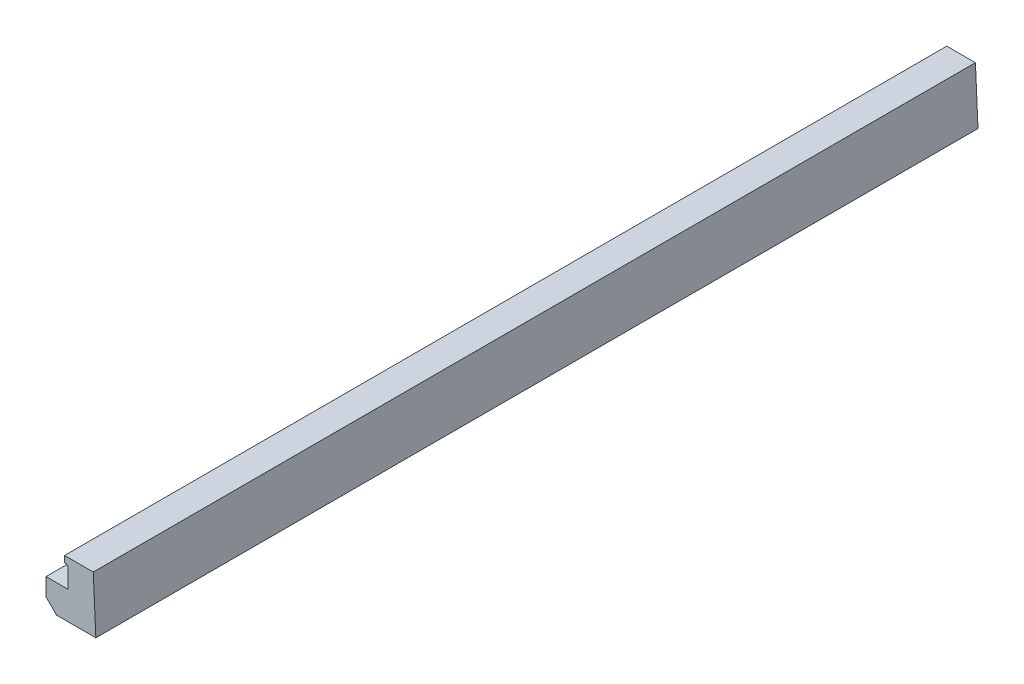
SolidWorks part; units mm, degrees
material "PET"
ref_plane "Front Plane" through (0, 0, 0) normal (0, 0, 1) x (1, 0, 0)
ref_plane "Top Plane" through (0, 0, 0) normal (0, 1, 0) x (1, 0, 0)
ref_plane "Right Plane" through (0, 0, 0) normal (1, 0, 0) x (0, 0, -1)
sketch "Sketch10" plane through (0, 0, 0) normal (0, 0, 1) x (1, 0, 0)
  line L0 (-0.9755, 4.9039) -> (-1.2681, 6.3751)
  line L1 (1.2681, 6.3751) -> (0.9755, 4.9039)
  line L2 (2.7779, 4.1573) -> (3.6112, 5.4046)
  line L3 (5.4046, 3.6112) -> (4.1573, 2.7779)
  line L4 (4.9039, 0.9755) -> (6.3751, 1.2681)
  line L5 (6.3751, -1.2681) -> (4.9039, -0.9755)
  line L6 (4.1573, -2.7779) -> (5.4046, -3.6112)
  line L7 (3.6112, -5.4046) -> (2.7779, -4.1573)
  line L8 (0.9755, -4.9039) -> (1.2681, -6.3751)
  line L9 (-1.2681, -6.3751) -> (-0.9755, -4.9039)
  line L10 (-2.7779, -4.1573) -> (-3.6112, -5.4046)
  line L11 (-5.4046, -3.6112) -> (-4.1573, -2.7779)
  line L12 (-4.9039, -0.9755) -> (-6.3751, -1.2681)
  line L13 (-6.3751, 1.2681) -> (-4.9039, 0.9755)
  line L14 (-4.1573, 2.7779) -> (-5.4046, 3.6112)
  line L15 (-3.6112, 5.4046) -> (-2.7779, 4.1573)
  line L16 (22.5, -6.3) -> (22.5, -19.5)
  line L17 (22, -5.8) -> (21, -5.8)
  line L18 (21, -5.8) -> (21, -5.5)
  line L19 (20.5, -5) -> (17.525, -5)
  line L20 (17.025, -5.5) -> (17.025, -9.55)
  line L21 (16.525, -10.05) -> (11.7571, -10.05)
  line L22 (11.4036, -9.9036) -> (6.6582, -5.1582)
  line L23 (11.4036, 9.9036) -> (6.6582, 5.1582)
  line L24 (17.025, 10.05) -> (11.7571, 10.05)
  line L25 (17.025, 5.5) -> (17.025, 10.05)
  line L26 (20.5, 5) -> (17.525, 5)
  line L27 (21, 5.8) -> (21, 5.5)
  line L28 (22, 5.8) -> (21, 5.8)
  line L29 (22.5, 19.5) -> (22.5, 6.3)
  line L30 (6.3, 22.5) -> (19.5, 22.5)
  line L31 (5.8, 22) -> (5.8, 21)
  line L32 (5.8, 21) -> (5.5, 21)
  line L33 (5, 20.5) -> (5, 17.525)
  line L34 (5.5, 17.025) -> (9.55, 17.025)
  line L35 (10.05, 16.525) -> (10.05, 11.7571)
  line L36 (9.9036, 11.4036) -> (5.1582, 6.6582)
  line L37 (-9.9036, 11.4036) -> (-5.1582, 6.6582)
  line L38 (-10.05, 16.525) -> (-10.05, 11.7571)
  line L39 (-5.5, 17.025) -> (-9.55, 17.025)
  line L40 (-5, 20.5) -> (-5, 17.525)
  line L41 (-5.8, 21) -> (-5.5, 21)
  line L42 (-5.8, 22) -> (-5.8, 21)
  line L43 (-19.5, 22.5) -> (-6.3, 22.5)
  line L44 (-22.5, 6.3) -> (-22.5, 19.5)
  line L45 (-22, 5.8) -> (-21, 5.8)
  line L46 (-21, 5.8) -> (-21, 5.5)
  line L47 (-20.5, 5) -> (-17.525, 5)
  line L48 (-17.025, 5.5) -> (-17.025, 9.55)
  line L49 (-16.525, 10.05) -> (-11.7571, 10.05)
  line L50 (-11.4036, 9.9036) -> (-6.6582, 5.1582)
  line L51 (-11.4036, -9.9036) -> (-6.6582, -5.1582)
  line L52 (-16.525, -10.05) -> (-11.7571, -10.05)
  line L53 (-17.025, -5.5) -> (-17.025, -9.55)
  line L54 (-20.5, -5) -> (-17.525, -5)
  line L55 (-21, -5.8) -> (-21, -5.5)
  line L56 (-22, -5.8) -> (-21, -5.8)
  line L57 (-22.5, -19.5) -> (-22.5, -6.3)
  line L58 (-6.3, -22.5) -> (-19.5, -22.5)
  line L59 (-5.8, -22) -> (-5.8, -21)
  line L60 (-5.8, -21) -> (-5.5, -21)
  line L61 (-5, -20.5) -> (-5, -17.525)
  line L62 (-5.5, -17.025) -> (-9.55, -17.025)
  line L63 (-10.05, -16.525) -> (-10.05, -11.7571)
  line L64 (-9.9036, -11.4036) -> (-5.1582, -6.6582)
  line L65 (9.9036, -11.4036) -> (5.1582, -6.6582)
  line L66 (10.05, -16.525) -> (10.05, -11.7571)
  line L67 (5.5, -17.025) -> (9.55, -17.025)
  line L68 (5, -20.5) -> (5, -17.525)
  line L69 (5.8, -21) -> (5.5, -21)
  line L70 (5.8, -22) -> (5.8, -21)
  line L71 (19.5, -22.5) -> (6.3, -22.5)
  line L72 (-18.025, 11.55) -> (-12.05, 11.55)
  line L73 (-18.525, 8.5375) -> (-18.525, 11.05)
  line L74 (-21, 8.5375) -> (-21, 19.5)
  line L75 (-19.5, 21) -> (-8.5375, 21)
  line L76 (-8.5375, 18.525) -> (-11.05, 18.525)
  line L77 (-11.55, 18.025) -> (-11.55, 12.05)
  line L78 (11.55, 18.025) -> (11.55, 12.05)
  line L79 (8.5375, 18.525) -> (11.05, 18.525)
  line L80 (8.5375, 21) -> (19.5, 21)
  line L81 (21, 19.5) -> (21, 8.5375)
  line L82 (18.525, 8.5375) -> (18.525, 11.05)
  line L83 (18.025, 11.55) -> (12.05, 11.55)
  line L84 (18.025, -11.55) -> (12.05, -11.55)
  line L85 (18.525, -8.5375) -> (18.525, -11.05)
  line L86 (21, -8.5375) -> (21, -19.5)
  line L87 (19.5, -21) -> (8.5375, -21)
  line L88 (8.5375, -18.525) -> (11.05, -18.525)
  line L89 (11.55, -18.025) -> (11.55, -12.05)
  line L90 (-11.55, -18.025) -> (-11.55, -12.05)
  line L91 (-8.5375, -18.525) -> (-11.05, -18.525)
  line L92 (-8.5375, -21) -> (-19.5, -21)
  line L93 (-21, -19.5) -> (-21, -8.5375)
  line L94 (-18.525, -8.5375) -> (-18.525, -11.55)
  line L95 (-18.525, -11.55) -> (-12.05, -11.55)
  line L96 (-22.5, 19.5) -> (-22.5, 24.5)
  line L97 (-22.5, 24.5) -> (24.5, 24.5)
  line L98 (24.5, 24.5) -> (24.5, -22.5)
  line L99 (24.5, -22.5) -> (19.5, -22.5)
  line L100 (8, 6.5) -> (8, -6.5)
  line L101 (-6.5, 8) -> (6.5, 8)
  arc A0 (0.9755, 4.9039) -> (-0.9755, 4.9039) centre (0, 0) ccw
  arc A1 (3.6112, 5.4046) -> (1.2681, 6.3751) centre (0, 0) ccw
  arc A2 (4.1573, 2.7779) -> (2.7779, 4.1573) centre (0, 0) ccw
  arc A3 (6.3751, 1.2681) -> (5.4046, 3.6112) centre (0, 0) ccw
  arc A4 (4.9039, -0.9755) -> (4.9039, 0.9755) centre (0, 0) ccw
  arc A5 (5.4046, -3.6112) -> (6.3751, -1.2681) centre (0, 0) ccw
  arc A6 (2.7779, -4.1573) -> (4.1573, -2.7779) centre (0, 0) ccw
  arc A7 (1.2681, -6.3751) -> (3.6112, -5.4046) centre (0, 0) ccw
  arc A8 (-0.9755, -4.9039) -> (0.9755, -4.9039) centre (0, 0) ccw
  arc A9 (-3.6112, -5.4046) -> (-1.2681, -6.3751) centre (0, 0) ccw
  arc A10 (-4.1573, -2.7779) -> (-2.7779, -4.1573) centre (0, 0) ccw
  arc A11 (-6.3751, -1.2681) -> (-5.4046, -3.6112) centre (0, 0) ccw
  arc A12 (-4.9039, 0.9755) -> (-4.9039, -0.9755) centre (0, 0) ccw
  arc A13 (-5.4046, 3.6112) -> (-6.3751, 1.2681) centre (0, 0) ccw
  arc A14 (-2.7779, 4.1573) -> (-4.1573, 2.7779) centre (0, 0) ccw
  arc A15 (-1.2681, 6.3751) -> (-3.6112, 5.4046) centre (0, 0) ccw
  arc A16 (22.5, -6.3) -> (22, -5.8) centre (22, -6.3) ccw
  arc A17 (21, -5.5) -> (20.5, -5) centre (20.5, -5.5) ccw
  arc A18 (17.525, -5) -> (17.025, -5.5) centre (17.525, -5.5) ccw
  arc A19 (16.525, -10.05) -> (17.025, -9.55) centre (16.525, -9.55) ccw
  arc A20 (11.4036, -9.9036) -> (11.7571, -10.05) centre (11.7571, -9.55) ccw
  arc A21 (6.5993, -4.522) -> (6.6582, -5.1582) centre (7.0118, -4.8047) ccw
  arc A22 (6.5993, -4.522) -> (6.5993, 4.522) centre (0, 0) ccw
  arc A23 (6.6582, 5.1582) -> (6.5993, 4.522) centre (7.0118, 4.8047) ccw
  arc A24 (11.7571, 10.05) -> (11.4036, 9.9036) centre (11.7571, 9.55) ccw
  arc A25 (17.025, 5.5) -> (17.525, 5) centre (17.525, 5.5) ccw
  arc A26 (20.5, 5) -> (21, 5.5) centre (20.5, 5.5) ccw
  arc A27 (22, 5.8) -> (22.5, 6.3) centre (22, 6.3) ccw
  arc A28 (22.5, 19.5) -> (19.5, 22.5) centre (19.5, 19.5) ccw
  arc A29 (6.3, 22.5) -> (5.8, 22) centre (6.3, 22) ccw
  arc A30 (5.5, 21) -> (5, 20.5) centre (5.5, 20.5) ccw
  arc A31 (5, 17.525) -> (5.5, 17.025) centre (5.5, 17.525) ccw
  arc A32 (10.05, 16.525) -> (9.55, 17.025) centre (9.55, 16.525) ccw
  arc A33 (9.9036, 11.4036) -> (10.05, 11.7571) centre (9.55, 11.7571) ccw
  arc A34 (4.522, 6.5993) -> (5.1582, 6.6582) centre (4.8047, 7.0118) ccw
  arc A35 (4.522, 6.5993) -> (-4.522, 6.5993) centre (0, 0) ccw
  arc A36 (-5.1582, 6.6582) -> (-4.522, 6.5993) centre (-4.8047, 7.0118) ccw
  arc A37 (-10.05, 11.7571) -> (-9.9036, 11.4036) centre (-9.55, 11.7571) ccw
  arc A38 (-9.55, 17.025) -> (-10.05, 16.525) centre (-9.55, 16.525) ccw
  arc A39 (-5.5, 17.025) -> (-5, 17.525) centre (-5.5, 17.525) ccw
  arc A40 (-5, 20.5) -> (-5.5, 21) centre (-5.5, 20.5) ccw
  arc A41 (-5.8, 22) -> (-6.3, 22.5) centre (-6.3, 22) ccw
  arc A42 (-19.5, 22.5) -> (-22.5, 19.5) centre (-19.5, 19.5) ccw
  arc A43 (-22.5, 6.3) -> (-22, 5.8) centre (-22, 6.3) ccw
  arc A44 (-21, 5.5) -> (-20.5, 5) centre (-20.5, 5.5) ccw
  arc A45 (-17.525, 5) -> (-17.025, 5.5) centre (-17.525, 5.5) ccw
  arc A46 (-16.525, 10.05) -> (-17.025, 9.55) centre (-16.525, 9.55) ccw
  arc A47 (-11.4036, 9.9036) -> (-11.7571, 10.05) centre (-11.7571, 9.55) ccw
  arc A48 (-6.5993, 4.522) -> (-6.6582, 5.1582) centre (-7.0118, 4.8047) ccw
  arc A49 (-6.5993, 4.522) -> (-6.5993, -4.522) centre (0, 0) ccw
  arc A50 (-6.6582, -5.1582) -> (-6.5993, -4.522) centre (-7.0118, -4.8047) ccw
  arc A51 (-11.7571, -10.05) -> (-11.4036, -9.9036) centre (-11.7571, -9.55) ccw
  arc A52 (-17.025, -9.55) -> (-16.525, -10.05) centre (-16.525, -9.55) ccw
  arc A53 (-17.025, -5.5) -> (-17.525, -5) centre (-17.525, -5.5) ccw
  arc A54 (-20.5, -5) -> (-21, -5.5) centre (-20.5, -5.5) ccw
  arc A55 (-22, -5.8) -> (-22.5, -6.3) centre (-22, -6.3) ccw
  arc A56 (-22.5, -19.5) -> (-19.5, -22.5) centre (-19.5, -19.5) ccw
  arc A57 (-6.3, -22.5) -> (-5.8, -22) centre (-6.3, -22) ccw
  arc A58 (-5.5, -21) -> (-5, -20.5) centre (-5.5, -20.5) ccw
  arc A59 (-5, -17.525) -> (-5.5, -17.025) centre (-5.5, -17.525) ccw
  arc A60 (-10.05, -16.525) -> (-9.55, -17.025) centre (-9.55, -16.525) ccw
  arc A61 (-9.9036, -11.4036) -> (-10.05, -11.7571) centre (-9.55, -11.7571) ccw
  arc A62 (-4.522, -6.5993) -> (-5.1582, -6.6582) centre (-4.8047, -7.0118) ccw
  arc A63 (-4.522, -6.5993) -> (4.522, -6.5993) centre (0, 0) ccw
  arc A64 (5.1582, -6.6582) -> (4.522, -6.5993) centre (4.8047, -7.0118) ccw
  arc A65 (10.05, -11.7571) -> (9.9036, -11.4036) centre (9.55, -11.7571) ccw
  arc A66 (9.55, -17.025) -> (10.05, -16.525) centre (9.55, -16.525) ccw
  arc A67 (5.5, -17.025) -> (5, -17.525) centre (5.5, -17.525) ccw
  arc A68 (5, -20.5) -> (5.5, -21) centre (5.5, -20.5) ccw
  arc A69 (5.8, -22) -> (6.3, -22.5) centre (6.3, -22) ccw
  arc A70 (19.5, -22.5) -> (22.5, -19.5) centre (19.5, -19.5) ccw
  arc A71 (-18.025, 11.55) -> (-18.525, 11.05) centre (-18.025, 11.05) ccw
  arc A72 (-21, 8.5375) -> (-18.525, 8.5375) centre (-19.7625, 8.5375) ccw
  arc A73 (-19.5, 21) -> (-21, 19.5) centre (-19.5, 19.5) ccw
  arc A74 (-8.5375, 18.525) -> (-8.5375, 21) centre (-8.5375, 19.7625) ccw
  arc A75 (-11.05, 18.525) -> (-11.55, 18.025) centre (-11.05, 18.025) ccw
  arc A76 (-12.05, 11.55) -> (-11.55, 12.05) centre (-12.05, 12.05) ccw
  arc A77 (11.55, 18.025) -> (11.05, 18.525) centre (11.05, 18.025) ccw
  arc A78 (8.5375, 21) -> (8.5375, 18.525) centre (8.5375, 19.7625) ccw
  arc A79 (21, 19.5) -> (19.5, 21) centre (19.5, 19.5) ccw
  arc A80 (18.525, 8.5375) -> (21, 8.5375) centre (19.7625, 8.5375) ccw
  arc A81 (18.525, 11.05) -> (18.025, 11.55) centre (18.025, 11.05) ccw
  arc A82 (11.55, 12.05) -> (12.05, 11.55) centre (12.05, 12.05) ccw
  arc A83 (18.025, -11.55) -> (18.525, -11.05) centre (18.025, -11.05) ccw
  arc A84 (21, -8.5375) -> (18.525, -8.5375) centre (19.7625, -8.5375) ccw
  arc A85 (19.5, -21) -> (21, -19.5) centre (19.5, -19.5) ccw
  arc A86 (8.5375, -18.525) -> (8.5375, -21) centre (8.5375, -19.7625) ccw
  arc A87 (11.05, -18.525) -> (11.55, -18.025) centre (11.05, -18.025) ccw
  arc A88 (12.05, -11.55) -> (11.55, -12.05) centre (12.05, -12.05) ccw
  arc A89 (-11.55, -18.025) -> (-11.05, -18.525) centre (-11.05, -18.025) ccw
  arc A90 (-8.5375, -21) -> (-8.5375, -18.525) centre (-8.5375, -19.7625) ccw
  arc A91 (-21, -19.5) -> (-19.5, -21) centre (-19.5, -19.5) ccw
  arc A92 (-18.525, -8.5375) -> (-21, -8.5375) centre (-19.7625, -8.5375) ccw
  arc A93 (-11.55, -12.05) -> (-12.05, -11.55) centre (-12.05, -12.05) ccw
  point P267 (8, 0)
  point P270 (0, 8)
  dimension "D1" = 45
  dimension "D2" = 45
  dimension "D3" = 47
extrude "Y-Rail Slot" add sketch "Sketch10" along normal mid plane 90 contours A70 L99 L98 L97 L96 A42 L43 A41 L42 L41 A40 L40 A39 L39 A38 L38 A37 L37 L101 L36 A33 L35 A32 L34 A31 L33 A30 L32 L31 A29 L30 A28 L29 A27 L28 L27 A26 L26 A25 L25 L24 A24 L23 L100 L22 A20 L21 A19 L20 region at (22.8236, -5.4764, 0)
sketch "Sketch12" plane through (0, 0, -45) normal (0, 0, -1) x (-1, 0, 0)
  line L30 (-22.5, -19.5) -> (-22.5, -6.3)
  line L42 (-22.5, -19.5) -> (-22.5, -6.3)
  line L44 (-22, -5.8) -> (-21, -5.8)
  line L46 (-22, -5.8) -> (-21, -5.8)
  line L48 (-21, -5.8) -> (-21, -5.5)
  line L50 (-21, -5.8) -> (-21, -5.5)
  line L52 (-20.5, -5) -> (-17.525, -5)
  line L54 (-20.5, -5) -> (-17.525, -5)
  line L56 (-17.025, -5.5) -> (-17.025, -9.55)
  line L109 (-17.025, -5.5) -> (-17.025, -9.55)
  line L122 (-16.525, -10.05) -> (-11.7571, -10.05)
  line L136 (-16.525, -10.05) -> (-11.7571, -10.05)
  line L146 (-11.4036, -9.9036) -> (-8, -6.5)
  line L150 (-11.4036, -9.9036) -> (-8, -6.5)
  line L154 (-8, -6.5) -> (-8, 6.5)
  line L158 (22.5, 19.5) -> (22.5, 24.5)
  line L159 (22.5, 19.5) -> (22.5, 24.5)
  line L160 (22.5, 24.5) -> (-24.5, 24.5)
  line L161 (22.5, 24.5) -> (-24.5, 24.5)
  line L162 (-24.5, 24.5) -> (-24.5, -22.5)
  line L163 (-24.5, 24.5) -> (-24.5, -22.5)
  line L164 (-24.5, -22.5) -> (-19.5, -22.5)
  line L165 (-24.5, -22.5) -> (-19.5, -22.5)
  line L166 (-8, -6.5) -> (-8, 6.5)
  line L168 (-8, 6.5) -> (-11.4036, 9.9036)
  line L170 (-8, 6.5) -> (-11.4036, 9.9036)
  line L172 (-11.7571, 10.05) -> (-17.025, 10.05)
  line L174 (-11.7571, 10.05) -> (-17.025, 10.05)
  line L176 (-17.025, 10.05) -> (-17.025, 5.5)
  line L178 (-17.025, 10.05) -> (-17.025, 5.5)
  line L180 (-17.525, 5) -> (-20.5, 5)
  line L182 (-17.525, 5) -> (-20.5, 5)
  line L184 (-21, 5.5) -> (-21, 5.8)
  line L186 (-21, 5.5) -> (-21, 5.8)
  line L188 (-21, 5.8) -> (-22, 5.8)
  line L190 (-21, 5.8) -> (-22, 5.8)
  line L192 (-22.5, 6.3) -> (-22.5, 19.5)
  line L194 (-22.5, 6.3) -> (-22.5, 19.5)
  line L196 (-19.5, 22.5) -> (-6.3, 22.5)
  line L197 (-19.5, 22.5) -> (-6.3, 22.5)
  line L198 (-5.8, 22) -> (-5.8, 21)
  line L199 (-5.8, 22) -> (-5.8, 21)
  line L200 (-5.8, 21) -> (-5.5, 21)
  line L201 (-5.8, 21) -> (-5.5, 21)
  line L202 (-5, 20.5) -> (-5, 17.525)
  line L203 (-5, 20.5) -> (-5, 17.525)
  line L204 (-5.5, 17.025) -> (-9.55, 17.025)
  line L205 (-5.5, 17.025) -> (-9.55, 17.025)
  line L206 (-10.05, 16.525) -> (-10.05, 11.7571)
  line L207 (-10.05, 16.525) -> (-10.05, 11.7571)
  line L208 (-9.9036, 11.4036) -> (-6.5, 8)
  line L209 (-9.9036, 11.4036) -> (-6.5, 8)
  line L210 (-6.5, 8) -> (6.5, 8)
  line L211 (-6.5, 8) -> (6.5, 8)
  line L212 (6.5, 8) -> (9.9036, 11.4036)
  line L213 (6.5, 8) -> (9.9036, 11.4036)
  line L214 (10.05, 11.7571) -> (10.05, 16.525)
  line L215 (10.05, 11.7571) -> (10.05, 16.525)
  line L216 (9.55, 17.025) -> (5.5, 17.025)
  line L217 (9.55, 17.025) -> (5.5, 17.025)
  line L218 (5, 17.525) -> (5, 20.5)
  line L219 (5, 17.525) -> (5, 20.5)
  line L220 (5.5, 21) -> (5.8, 21)
  line L221 (5.5, 21) -> (5.8, 21)
  line L222 (5.8, 21) -> (5.8, 22)
  line L223 (5.8, 21) -> (5.8, 22)
  line L224 (6.3, 22.5) -> (19.5, 22.5)
  line L225 (6.3, 22.5) -> (19.5, 22.5)
  arc A20 (-22.5, -19.5) -> (-19.5, -22.5) centre (-19.5, -19.5) ccw
  arc A29 (-22.5, -19.5) -> (-19.5, -22.5) centre (-19.5, -19.5) ccw
  arc A31 (-22, -5.8) -> (-22.5, -6.3) centre (-22, -6.3) ccw
  arc A33 (-22, -5.8) -> (-22.5, -6.3) centre (-22, -6.3) ccw
  arc A35 (-20.5, -5) -> (-21, -5.5) centre (-20.5, -5.5) ccw
  arc A37 (-20.5, -5) -> (-21, -5.5) centre (-20.5, -5.5) ccw
  arc A76 (-17.025, -5.5) -> (-17.525, -5) centre (-17.525, -5.5) ccw
  arc A90 (-17.025, -5.5) -> (-17.525, -5) centre (-17.525, -5.5) ccw
  arc A98 (-17.025, -9.55) -> (-16.525, -10.05) centre (-16.525, -9.55) ccw
  arc A102 (-17.025, -9.55) -> (-16.525, -10.05) centre (-16.525, -9.55) ccw
  arc A106 (-11.7571, -10.05) -> (-11.4036, -9.9036) centre (-11.7571, -9.55) ccw
  arc A110 (-11.7571, -10.05) -> (-11.4036, -9.9036) centre (-11.7571, -9.55) ccw
  arc A112 (-11.4036, 9.9036) -> (-11.7571, 10.05) centre (-11.7571, 9.55) ccw
  arc A114 (-11.4036, 9.9036) -> (-11.7571, 10.05) centre (-11.7571, 9.55) ccw
  arc A116 (-17.525, 5) -> (-17.025, 5.5) centre (-17.525, 5.5) ccw
  arc A118 (-17.525, 5) -> (-17.025, 5.5) centre (-17.525, 5.5) ccw
  arc A120 (-21, 5.5) -> (-20.5, 5) centre (-20.5, 5.5) ccw
  arc A122 (-21, 5.5) -> (-20.5, 5) centre (-20.5, 5.5) ccw
  arc A124 (-22.5, 6.3) -> (-22, 5.8) centre (-22, 6.3) ccw
  arc A126 (-22.5, 6.3) -> (-22, 5.8) centre (-22, 6.3) ccw
  arc A128 (-19.5, 22.5) -> (-22.5, 19.5) centre (-19.5, 19.5) ccw
  arc A130 (-19.5, 22.5) -> (-22.5, 19.5) centre (-19.5, 19.5) ccw
  arc A132 (-5.8, 22) -> (-6.3, 22.5) centre (-6.3, 22) ccw
  arc A133 (-5.8, 22) -> (-6.3, 22.5) centre (-6.3, 22) ccw
  arc A134 (-5, 20.5) -> (-5.5, 21) centre (-5.5, 20.5) ccw
  arc A135 (-5, 20.5) -> (-5.5, 21) centre (-5.5, 20.5) ccw
  arc A136 (-5.5, 17.025) -> (-5, 17.525) centre (-5.5, 17.525) ccw
  arc A137 (-5.5, 17.025) -> (-5, 17.525) centre (-5.5, 17.525) ccw
  arc A138 (-9.55, 17.025) -> (-10.05, 16.525) centre (-9.55, 16.525) ccw
  arc A139 (-9.55, 17.025) -> (-10.05, 16.525) centre (-9.55, 16.525) ccw
  arc A140 (-10.05, 11.7571) -> (-9.9036, 11.4036) centre (-9.55, 11.7571) ccw
  arc A141 (-10.05, 11.7571) -> (-9.9036, 11.4036) centre (-9.55, 11.7571) ccw
  arc A142 (9.9036, 11.4036) -> (10.05, 11.7571) centre (9.55, 11.7571) ccw
  arc A143 (9.9036, 11.4036) -> (10.05, 11.7571) centre (9.55, 11.7571) ccw
  arc A144 (10.05, 16.525) -> (9.55, 17.025) centre (9.55, 16.525) ccw
  arc A145 (10.05, 16.525) -> (9.55, 17.025) centre (9.55, 16.525) ccw
  arc A146 (5, 17.525) -> (5.5, 17.025) centre (5.5, 17.525) ccw
  arc A147 (5, 17.525) -> (5.5, 17.025) centre (5.5, 17.525) ccw
  arc A148 (5.5, 21) -> (5, 20.5) centre (5.5, 20.5) ccw
  arc A149 (5.5, 21) -> (5, 20.5) centre (5.5, 20.5) ccw
  arc A150 (6.3, 22.5) -> (5.8, 22) centre (6.3, 22) ccw
  arc A151 (6.3, 22.5) -> (5.8, 22) centre (6.3, 22) ccw
  arc A152 (22.5, 19.5) -> (19.5, 22.5) centre (19.5, 19.5) ccw
  arc A153 (22.5, 19.5) -> (19.5, 22.5) centre (19.5, 19.5) ccw
  dimension "D1" = 0
extrude "Y-Rail cont." add sketch "Sketch12" along normal blind 2
sketch "Sketch17" plane through (0, 24.5, 0) normal (0, 1, 0) x (1, 0, 0)
  line L0 (19.5, -45) -> (24.5, -45)
  line L1 (24.5, -45) -> (24.5, 2)
  line L2 (24.5, 2) -> (-22.5, 2)
  line L3 (-22.5, 2) -> (-22.5, -3)
  line L4 (-19.5, 0) -> (-6.3, 0)
  line L5 (-5.8, -0.5) -> (-5.8, -1.5)
  line L6 (-5.8, -1.5) -> (-5.5, -1.5)
  line L7 (-5, -2) -> (-5, -4.975)
  line L8 (-5.5, -5.475) -> (-9.55, -5.475)
  line L9 (-10.05, -5.975) -> (-10.05, -10.7429)
  line L10 (-9.9036, -11.0964) -> (-6.5, -14.5)
  line L11 (-6.5, -14.5) -> (6.5, -14.5)
  line L12 (6.5, -14.5) -> (9.9036, -11.0964)
  line L13 (10.05, -10.7429) -> (10.05, -5.975)
  line L14 (9.55, -5.475) -> (5.5, -5.475)
  line L15 (5, -4.975) -> (5, -2)
  line L16 (5.5, -1.5) -> (5.8, -1.5)
  line L17 (5.8, -1.5) -> (5.8, -0.5)
  line L18 (6.3, 0) -> (19.5, 0)
  line L19 (22.5, -3) -> (22.5, -16.2)
  line L20 (22, -16.7) -> (21, -16.7)
  line L21 (21, -16.7) -> (21, -17)
  line L22 (20.5, -17.5) -> (17.525, -17.5)
  line L23 (17.025, -17) -> (17.025, -12.45)
  line L24 (17.025, -12.45) -> (11.7571, -12.45)
  line L25 (11.4036, -12.5964) -> (8, -16)
  line L26 (8, -16) -> (8, -29)
  line L27 (8, -29) -> (11.4036, -32.4036)
  line L28 (11.7571, -32.55) -> (16.525, -32.55)
  line L29 (17.025, -32.05) -> (17.025, -28)
  line L30 (17.525, -27.5) -> (20.5, -27.5)
  line L31 (21, -28) -> (21, -28.3)
  line L32 (21, -28.3) -> (22, -28.3)
  line L33 (22.5, -28.8) -> (22.5, -42)
  arc A0 (19.5, -45) -> (22.5, -42) centre (19.5, -42) ccw
  arc A1 (-19.5, 0) -> (-22.5, -3) centre (-19.5, -3) ccw
  arc A2 (-5.8, -0.5) -> (-6.3, 0) centre (-6.3, -0.5) ccw
  arc A3 (-5, -2) -> (-5.5, -1.5) centre (-5.5, -2) ccw
  arc A4 (-5.5, -5.475) -> (-5, -4.975) centre (-5.5, -4.975) ccw
  arc A5 (-9.55, -5.475) -> (-10.05, -5.975) centre (-9.55, -5.975) ccw
  arc A6 (-10.05, -10.7429) -> (-9.9036, -11.0964) centre (-9.55, -10.7429) ccw
  arc A7 (9.9036, -11.0964) -> (10.05, -10.7429) centre (9.55, -10.7429) ccw
  arc A8 (10.05, -5.975) -> (9.55, -5.475) centre (9.55, -5.975) ccw
  arc A9 (5, -4.975) -> (5.5, -5.475) centre (5.5, -4.975) ccw
  arc A10 (5.5, -1.5) -> (5, -2) centre (5.5, -2) ccw
  arc A11 (6.3, 0) -> (5.8, -0.5) centre (6.3, -0.5) ccw
  arc A12 (22.5, -3) -> (19.5, 0) centre (19.5, -3) ccw
  arc A13 (22, -16.7) -> (22.5, -16.2) centre (22, -16.2) ccw
  arc A14 (20.5, -17.5) -> (21, -17) centre (20.5, -17) ccw
  arc A15 (17.025, -17) -> (17.525, -17.5) centre (17.525, -17) ccw
  arc A16 (11.7571, -12.45) -> (11.4036, -12.5964) centre (11.7571, -12.95) ccw
  arc A17 (11.4036, -32.4036) -> (11.7571, -32.55) centre (11.7571, -32.05) ccw
  arc A18 (16.525, -32.55) -> (17.025, -32.05) centre (16.525, -32.05) ccw
  arc A19 (17.525, -27.5) -> (17.025, -28) centre (17.525, -28) ccw
  arc A20 (21, -28) -> (20.5, -27.5) centre (20.5, -28) ccw
  arc A21 (22.5, -28.8) -> (22, -28.3) centre (22, -28.8) ccw
extrude "Z-Rail Slot" add sketch "Sketch17" along normal blind 45
sketch "Sketch11" plane through (24.5, 0, 0) normal (1, 0, 0) x (0, 0, -1)
  line L0 (-5.95, -19.5) -> (5.95, -19.5)
  line L1 (-10.95, -11.7571) -> (-10.95, -14.5)
  line L2 (-11.8642, -10.0145) -> (-11.5358, -10.3429)
  line L3 (-12.45, 8.6003) -> (-12.45, -8.6003)
  line L4 (-11.8642, 10.0145) -> (-11.5358, 10.3429)
  line L5 (-10.95, 11.7571) -> (-10.95, 14.5)
  line L6 (-5.95, 19.5) -> (5.95, 19.5)
  line L7 (10.95, 11.7571) -> (10.95, 14.5)
  line L8 (11.8642, 10.0145) -> (11.5358, 10.3429)
  line L9 (12.45, 8.6003) -> (12.45, -8.6003)
  line L10 (11.8642, -10.0145) -> (11.5358, -10.3429)
  line L11 (10.95, -11.7571) -> (10.95, -14.5)
  line L12 (-27.4039, -0.9755) -> (-28.8751, -1.2681)
  line L13 (-28.8751, 1.2681) -> (-27.4039, 0.9755)
  line L14 (-26.6573, 2.7779) -> (-27.9046, 3.6112)
  line L15 (-26.1112, 5.4046) -> (-25.2779, 4.1573)
  line L16 (-23.4755, 4.9039) -> (-23.7681, 6.3751)
  line L17 (-21.2319, 6.3751) -> (-21.5245, 4.9039)
  line L18 (-19.7221, 4.1573) -> (-18.8888, 5.4046)
  line L19 (-17.0954, 3.6112) -> (-18.3427, 2.7779)
  line L20 (-17.5961, 0.9755) -> (-16.1249, 1.2681)
  line L21 (-16.1249, -1.2681) -> (-17.5961, -0.9755)
  line L22 (-18.3427, -2.7779) -> (-17.0954, -3.6112)
  line L23 (-18.8888, -5.4046) -> (-19.7221, -4.1573)
  line L24 (-21.5245, -4.9039) -> (-21.2319, -6.3751)
  line L25 (-23.7681, -6.3751) -> (-23.4755, -4.9039)
  line L26 (-25.2779, -4.1573) -> (-26.1112, -5.4046)
  line L27 (-27.9046, -3.6112) -> (-26.6573, -2.7779)
  line L28 (-40.525, 11.55) -> (-34.55, 11.55)
  line L29 (-41.025, 8.5375) -> (-41.025, 11.05)
  line L30 (-43.5, 8.5375) -> (-43.5, 19.5)
  line L31 (-42, 21) -> (-31.0375, 21)
  line L32 (-31.0375, 18.525) -> (-33.55, 18.525)
  line L33 (-34.05, 18.025) -> (-34.05, 12.05)
  line L34 (-34.05, -18.025) -> (-34.05, -12.05)
  line L35 (-31.0375, -18.525) -> (-33.55, -18.525)
  line L36 (-31.0375, -21) -> (-42, -21)
  line L37 (-43.5, -19.5) -> (-43.5, -8.5375)
  line L38 (-41.025, -8.5375) -> (-41.025, -11.05)
  line L39 (-40.525, -11.55) -> (-34.55, -11.55)
  line L40 (16.7, 22) -> (16.7, 21)
  line L41 (16.2, 22.5) -> (7.8, 22.5)
  line L42 (7.8, 22.5) -> (7.8, 21.5)
  line L43 (-7.3, 21) -> (7.3, 21)
  line L44 (-7.8, 22.5) -> (-7.8, 21.5)
  line L45 (-16.2, 22.5) -> (-7.8, 22.5)
  line L46 (-16.7, 22) -> (-16.7, 21)
  line L47 (-16.7, 21) -> (-17, 21)
  line L48 (-17.5, 20.5) -> (-17.5, 17.525)
  line L49 (-17, 17.025) -> (-12.95, 17.025)
  line L50 (-12.45, 16.525) -> (-12.45, 11.7571)
  line L51 (-12.5964, 11.4036) -> (-17.3418, 6.6582)
  line L52 (-32.4036, 11.4036) -> (-27.6582, 6.6582)
  line L53 (-32.55, 17.025) -> (-32.55, 11.7571)
  line L54 (-28, 17.025) -> (-32.55, 17.025)
  line L55 (-27.5, 20.5) -> (-27.5, 17.525)
  line L56 (-28.3, 21) -> (-28, 21)
  line L57 (-28.3, 22) -> (-28.3, 21)
  line L58 (-42, 22.5) -> (-28.8, 22.5)
  line L59 (-45, 6.3) -> (-45, 19.5)
  line L60 (-44.5, 5.8) -> (-43.5, 5.8)
  line L61 (-43.5, 5.8) -> (-43.5, 5.5)
  line L62 (-43, 5) -> (-40.025, 5)
  line L63 (-39.525, 5.5) -> (-39.525, 9.55)
  line L64 (-39.025, 10.05) -> (-34.2571, 10.05)
  line L65 (-33.9036, 9.9036) -> (-29.1582, 5.1582)
  line L66 (-33.9036, -9.9036) -> (-29.1582, -5.1582)
  line L67 (-39.025, -10.05) -> (-34.2571, -10.05)
  line L68 (-39.525, -5.5) -> (-39.525, -9.55)
  line L69 (-43, -5) -> (-40.025, -5)
  line L70 (-43.5, -5.8) -> (-43.5, -5.5)
  line L71 (-44.5, -5.8) -> (-43.5, -5.8)
  line L72 (-45, -19.5) -> (-45, -6.3)
  line L73 (-28.8, -22.5) -> (-42, -22.5)
  line L74 (-28.3, -22) -> (-28.3, -21)
  line L75 (-28.3, -21) -> (-28, -21)
  line L76 (-27.5, -20.5) -> (-27.5, -17.525)
  line L77 (-28, -17.025) -> (-32.05, -17.025)
  line L78 (-32.55, -16.525) -> (-32.55, -11.7571)
  line L79 (-32.4036, -11.4036) -> (-27.6582, -6.6582)
  line L80 (-12.5964, -11.4036) -> (-17.3418, -6.6582)
  line L81 (-12.45, -16.525) -> (-12.45, -11.7571)
  line L82 (-17, -17.025) -> (-12.95, -17.025)
  line L83 (-17.5, -20.5) -> (-17.5, -17.525)
  line L84 (-16.7, -21) -> (-17, -21)
  line L85 (-16.7, -22) -> (-16.7, -21)
  line L86 (-7.8, -22.5) -> (-16.2, -22.5)
  line L87 (-7.8, -22.5) -> (-7.8, -21.5)
  line L88 (-7.3, -21) -> (7.3, -21)
  line L89 (7.8, -22.5) -> (7.8, -21.5)
  line L90 (7.8, -22.5) -> (16.2, -22.5)
  line L91 (16.7, -22) -> (16.7, -21)
  line L92 (16.7, -21) -> (17, -21)
  line L93 (17.5, -20.5) -> (17.5, -17.525)
  line L94 (17, -17.025) -> (12.95, -17.025)
  line L95 (12.45, -16.525) -> (12.45, -11.7571)
  line L96 (12.5964, -11.4036) -> (17.3418, -6.6582)
  line L97 (32.4036, -11.4036) -> (27.6582, -6.6582)
  line L98 (32.55, -16.525) -> (32.55, -11.7571)
  line L99 (28, -17.025) -> (32.05, -17.025)
  line L100 (27.5, -20.5) -> (27.5, -17.525)
  line L101 (28.3, -21) -> (28, -21)
  line L102 (28.3, -22) -> (28.3, -21)
  line L103 (28.8, -22.5) -> (42, -22.5)
  line L104 (45, -19.5) -> (45, -6.3)
  line L105 (44.5, -5.8) -> (43.5, -5.8)
  line L106 (43.5, -5.8) -> (43.5, -5.5)
  line L107 (43, -5) -> (40.025, -5)
  line L108 (39.525, -5.5) -> (39.525, -9.55)
  line L109 (39.025, -10.05) -> (34.2571, -10.05)
  line L110 (33.9036, -9.9036) -> (29.1582, -5.1582)
  line L111 (33.9036, 9.9036) -> (29.1582, 5.1582)
  line L112 (39.025, 10.05) -> (34.2571, 10.05)
  line L113 (39.525, 5.5) -> (39.525, 9.55)
  line L114 (43, 5) -> (40.025, 5)
  line L115 (43.5, 5.8) -> (43.5, 5.5)
  line L116 (44.5, 5.8) -> (43.5, 5.8)
  line L117 (45, 6.3) -> (45, 19.5)
  line L118 (42, 22.5) -> (28.8, 22.5)
  line L119 (28.3, 22) -> (28.3, 21)
  line L120 (28.3, 21) -> (28, 21)
  line L121 (27.5, 20.5) -> (27.5, 17.525)
  line L122 (28, 17.025) -> (32.55, 17.025)
  line L123 (32.55, 17.025) -> (32.55, 11.7571)
  line L124 (32.4036, 11.4036) -> (27.6582, 6.6582)
  line L125 (12.5964, 11.4036) -> (17.3418, 6.6582)
  line L126 (12.45, 16.525) -> (12.45, 11.7571)
  line L127 (17, 17.025) -> (12.95, 17.025)
  line L128 (17.5, 20.5) -> (17.5, 17.525)
  line L129 (16.7, 21) -> (17, 21)
  line L130 (41.025, 8.5375) -> (41.025, 11.05)
  line L131 (40.525, 11.55) -> (34.55, 11.55)
  line L132 (34.05, 18.025) -> (34.05, 12.05)
  line L133 (31.0375, 18.525) -> (33.55, 18.525)
  line L134 (42, 21) -> (31.0375, 21)
  line L135 (43.5, 8.5375) -> (43.5, 19.5)
  line L136 (31.0375, -18.525) -> (33.55, -18.525)
  line L137 (34.05, -18.025) -> (34.05, -12.05)
  line L138 (40.525, -11.55) -> (34.55, -11.55)
  line L139 (41.025, -8.5375) -> (41.025, -11.05)
  line L140 (43.5, -19.5) -> (43.5, -8.5375)
  line L141 (31.0375, -21) -> (42, -21)
  line L142 (27.9046, -3.6112) -> (26.6573, -2.7779)
  line L143 (25.2779, -4.1573) -> (26.1112, -5.4046)
  line L144 (23.7681, -6.3751) -> (23.4755, -4.9039)
  line L145 (21.5245, -4.9039) -> (21.2319, -6.3751)
  line L146 (18.8888, -5.4046) -> (19.7221, -4.1573)
  line L147 (18.3427, -2.7779) -> (17.0954, -3.6112)
  line L148 (16.1249, -1.2681) -> (17.5961, -0.9755)
  line L149 (17.5961, 0.9755) -> (16.1249, 1.2681)
  line L150 (17.0954, 3.6112) -> (18.3427, 2.7779)
  line L151 (19.7221, 4.1573) -> (18.8888, 5.4046)
  line L152 (21.2319, 6.3751) -> (21.5245, 4.9039)
  line L153 (23.4755, 4.9039) -> (23.7681, 6.3751)
  line L154 (26.1112, 5.4046) -> (25.2779, 4.1573)
  line L155 (26.6573, 2.7779) -> (27.9046, 3.6112)
  line L156 (28.8751, 1.2681) -> (27.4039, 0.9755)
  line L157 (27.4039, -0.9755) -> (28.8751, -1.2681)
  line L158 (-45, 69.5) -> (-45, -22.5) construction
  line L160 (-45, 19.5) -> (-45, 6.3)
  line L162 (-45, -6.3) -> (-45, -19.5)
  line L163 (47, 24.5) -> (47, -22.5)
  line L164 (-45, -22.5) -> (47, -22.5) construction
  line L165 (47, -22.5) -> (42, -22.5)
  line L166 (47, 24.5) -> (-45, 24.5)
  line L167 (-45, 24.5) -> (-45, 19.5)
  line L168 (-29, 8) -> (-16, 8)
  line L169 (16, 8) -> (29, 8)
  line L170 (30.5, 6.5) -> (30.5, -6.5)
  arc A0 (5.95, -19.5) -> (10.95, -14.5) centre (5.95, -14.5) ccw
  arc A1 (-10.95, -14.5) -> (-5.95, -19.5) centre (-5.95, -14.5) ccw
  arc A2 (-10.95, -11.7571) -> (-11.5358, -10.3429) centre (-12.95, -11.7571) ccw
  arc A3 (-12.45, -8.6003) -> (-11.8642, -10.0145) centre (-10.45, -8.6003) ccw
  arc A4 (-11.8642, 10.0145) -> (-12.45, 8.6003) centre (-10.45, 8.6003) ccw
  arc A5 (-11.5358, 10.3429) -> (-10.95, 11.7571) centre (-12.95, 11.7571) ccw
  arc A6 (-5.95, 19.5) -> (-10.95, 14.5) centre (-5.95, 14.5) ccw
  arc A7 (10.95, 14.5) -> (5.95, 19.5) centre (5.95, 14.5) ccw
  arc A8 (10.95, 11.7571) -> (11.5358, 10.3429) centre (12.95, 11.7571) ccw
  arc A9 (12.45, 8.6003) -> (11.8642, 10.0145) centre (10.45, 8.6003) ccw
  arc A10 (11.8642, -10.0145) -> (12.45, -8.6003) centre (10.45, -8.6003) ccw
  arc A11 (11.5358, -10.3429) -> (10.95, -11.7571) centre (12.95, -11.7571) ccw
  arc A12 (-27.4039, 0.9755) -> (-27.4039, -0.9755) centre (-22.5, 0) ccw
  arc A13 (-27.9046, 3.6112) -> (-28.8751, 1.2681) centre (-22.5, 0) ccw
  arc A14 (-25.2779, 4.1573) -> (-26.6573, 2.7779) centre (-22.5, 0) ccw
  arc A15 (-23.7681, 6.3751) -> (-26.1112, 5.4046) centre (-22.5, 0) ccw
  arc A16 (-21.5245, 4.9039) -> (-23.4755, 4.9039) centre (-22.5, 0) ccw
  arc A17 (-18.8888, 5.4046) -> (-21.2319, 6.3751) centre (-22.5, 0) ccw
  arc A18 (-18.3427, 2.7779) -> (-19.7221, 4.1573) centre (-22.5, 0) ccw
  arc A19 (-16.1249, 1.2681) -> (-17.0954, 3.6112) centre (-22.5, 0) ccw
  arc A20 (-17.5961, -0.9755) -> (-17.5961, 0.9755) centre (-22.5, 0) ccw
  arc A21 (-17.0954, -3.6112) -> (-16.1249, -1.2681) centre (-22.5, 0) ccw
  arc A22 (-19.7221, -4.1573) -> (-18.3427, -2.7779) centre (-22.5, 0) ccw
  arc A23 (-21.2319, -6.3751) -> (-18.8888, -5.4046) centre (-22.5, 0) ccw
  arc A24 (-23.4755, -4.9039) -> (-21.5245, -4.9039) centre (-22.5, 0) ccw
  arc A25 (-26.1112, -5.4046) -> (-23.7681, -6.3751) centre (-22.5, 0) ccw
  arc A26 (-26.6573, -2.7779) -> (-25.2779, -4.1573) centre (-22.5, 0) ccw
  arc A27 (-28.8751, -1.2681) -> (-27.9046, -3.6112) centre (-22.5, 0) ccw
  arc A28 (-40.525, 11.55) -> (-41.025, 11.05) centre (-40.525, 11.05) ccw
  arc A29 (-43.5, 8.5375) -> (-41.025, 8.5375) centre (-42.2625, 8.5375) ccw
  arc A30 (-42, 21) -> (-43.5, 19.5) centre (-42, 19.5) ccw
  arc A31 (-31.0375, 18.525) -> (-31.0375, 21) centre (-31.0375, 19.7625) ccw
  arc A32 (-33.55, 18.525) -> (-34.05, 18.025) centre (-33.55, 18.025) ccw
  arc A33 (-34.55, 11.55) -> (-34.05, 12.05) centre (-34.55, 12.05) ccw
  arc A34 (-34.05, -18.025) -> (-33.55, -18.525) centre (-33.55, -18.025) ccw
  arc A35 (-31.0375, -21) -> (-31.0375, -18.525) centre (-31.0375, -19.7625) ccw
  arc A36 (-43.5, -19.5) -> (-42, -21) centre (-42, -19.5) ccw
  arc A37 (-41.025, -8.5375) -> (-43.5, -8.5375) centre (-42.2625, -8.5375) ccw
  arc A38 (-41.025, -11.05) -> (-40.525, -11.55) centre (-40.525, -11.05) ccw
  arc A39 (-34.05, -12.05) -> (-34.55, -11.55) centre (-34.55, -12.05) ccw
  arc A40 (16.7, 22) -> (16.2, 22.5) centre (16.2, 22) ccw
  arc A41 (7.3, 21) -> (7.8, 21.5) centre (7.3, 21.5) ccw
  arc A42 (-7.8, 21.5) -> (-7.3, 21) centre (-7.3, 21.5) ccw
  arc A43 (-16.2, 22.5) -> (-16.7, 22) centre (-16.2, 22) ccw
  arc A44 (-17, 21) -> (-17.5, 20.5) centre (-17, 20.5) ccw
  arc A45 (-17.5, 17.525) -> (-17, 17.025) centre (-17, 17.525) ccw
  arc A46 (-12.45, 16.525) -> (-12.95, 17.025) centre (-12.95, 16.525) ccw
  arc A47 (-12.5964, 11.4036) -> (-12.45, 11.7571) centre (-12.95, 11.7571) ccw
  arc A48 (-17.978, 6.5993) -> (-17.3418, 6.6582) centre (-17.6953, 7.0118) ccw
  arc A49 (-17.978, 6.5993) -> (-27.022, 6.5993) centre (-22.5, 0) ccw
  arc A50 (-27.6582, 6.6582) -> (-27.022, 6.5993) centre (-27.3047, 7.0118) ccw
  arc A51 (-32.55, 11.7571) -> (-32.4036, 11.4036) centre (-32.05, 11.7571) ccw
  arc A52 (-28, 17.025) -> (-27.5, 17.525) centre (-28, 17.525) ccw
  arc A53 (-27.5, 20.5) -> (-28, 21) centre (-28, 20.5) ccw
  arc A54 (-28.3, 22) -> (-28.8, 22.5) centre (-28.8, 22) ccw
  arc A55 (-42, 22.5) -> (-45, 19.5) centre (-42, 19.5) ccw
  arc A56 (-45, 6.3) -> (-44.5, 5.8) centre (-44.5, 6.3) ccw
  arc A57 (-43.5, 5.5) -> (-43, 5) centre (-43, 5.5) ccw
  arc A58 (-40.025, 5) -> (-39.525, 5.5) centre (-40.025, 5.5) ccw
  arc A59 (-39.025, 10.05) -> (-39.525, 9.55) centre (-39.025, 9.55) ccw
  arc A60 (-33.9036, 9.9036) -> (-34.2571, 10.05) centre (-34.2571, 9.55) ccw
  arc A61 (-29.0993, 4.522) -> (-29.1582, 5.1582) centre (-29.5118, 4.8047) ccw
  arc A62 (-29.0993, 4.522) -> (-29.0993, -4.522) centre (-22.5, 0) ccw
  arc A63 (-29.1582, -5.1582) -> (-29.0993, -4.522) centre (-29.5118, -4.8047) ccw
  arc A64 (-34.2571, -10.05) -> (-33.9036, -9.9036) centre (-34.2571, -9.55) ccw
  arc A65 (-39.525, -9.55) -> (-39.025, -10.05) centre (-39.025, -9.55) ccw
  arc A66 (-39.525, -5.5) -> (-40.025, -5) centre (-40.025, -5.5) ccw
  arc A67 (-43, -5) -> (-43.5, -5.5) centre (-43, -5.5) ccw
  arc A68 (-44.5, -5.8) -> (-45, -6.3) centre (-44.5, -6.3) ccw
  arc A69 (-45, -19.5) -> (-42, -22.5) centre (-42, -19.5) ccw
  arc A70 (-28.8, -22.5) -> (-28.3, -22) centre (-28.8, -22) ccw
  arc A71 (-28, -21) -> (-27.5, -20.5) centre (-28, -20.5) ccw
  arc A72 (-27.5, -17.525) -> (-28, -17.025) centre (-28, -17.525) ccw
  arc A73 (-32.55, -16.525) -> (-32.05, -17.025) centre (-32.05, -16.525) ccw
  arc A74 (-32.4036, -11.4036) -> (-32.55, -11.7571) centre (-32.05, -11.7571) ccw
  arc A75 (-27.022, -6.5993) -> (-27.6582, -6.6582) centre (-27.3047, -7.0118) ccw
  arc A76 (-27.022, -6.5993) -> (-17.978, -6.5993) centre (-22.5, 0) ccw
  arc A77 (-17.3418, -6.6582) -> (-17.978, -6.5993) centre (-17.6953, -7.0118) ccw
  arc A78 (-12.45, -11.7571) -> (-12.5964, -11.4036) centre (-12.95, -11.7571) ccw
  arc A79 (-12.95, -17.025) -> (-12.45, -16.525) centre (-12.95, -16.525) ccw
  arc A80 (-17, -17.025) -> (-17.5, -17.525) centre (-17, -17.525) ccw
  arc A81 (-17.5, -20.5) -> (-17, -21) centre (-17, -20.5) ccw
  arc A82 (-16.7, -22) -> (-16.2, -22.5) centre (-16.2, -22) ccw
  arc A83 (-7.3, -21) -> (-7.8, -21.5) centre (-7.3, -21.5) ccw
  arc A84 (7.8, -21.5) -> (7.3, -21) centre (7.3, -21.5) ccw
  arc A85 (16.2, -22.5) -> (16.7, -22) centre (16.2, -22) ccw
  arc A86 (17, -21) -> (17.5, -20.5) centre (17, -20.5) ccw
  arc A87 (17.5, -17.525) -> (17, -17.025) centre (17, -17.525) ccw
  arc A88 (12.45, -16.525) -> (12.95, -17.025) centre (12.95, -16.525) ccw
  arc A89 (12.5964, -11.4036) -> (12.45, -11.7571) centre (12.95, -11.7571) ccw
  arc A90 (17.978, -6.5993) -> (17.3418, -6.6582) centre (17.6953, -7.0118) ccw
  arc A91 (17.978, -6.5993) -> (27.022, -6.5993) centre (22.5, 0) ccw
  arc A92 (27.6582, -6.6582) -> (27.022, -6.5993) centre (27.3047, -7.0118) ccw
  arc A93 (32.55, -11.7571) -> (32.4036, -11.4036) centre (32.05, -11.7571) ccw
  arc A94 (32.05, -17.025) -> (32.55, -16.525) centre (32.05, -16.525) ccw
  arc A95 (28, -17.025) -> (27.5, -17.525) centre (28, -17.525) ccw
  arc A96 (27.5, -20.5) -> (28, -21) centre (28, -20.5) ccw
  arc A97 (28.3, -22) -> (28.8, -22.5) centre (28.8, -22) ccw
  arc A98 (42, -22.5) -> (45, -19.5) centre (42, -19.5) ccw
  arc A99 (45, -6.3) -> (44.5, -5.8) centre (44.5, -6.3) ccw
  arc A100 (43.5, -5.5) -> (43, -5) centre (43, -5.5) ccw
  arc A101 (40.025, -5) -> (39.525, -5.5) centre (40.025, -5.5) ccw
  arc A102 (39.025, -10.05) -> (39.525, -9.55) centre (39.025, -9.55) ccw
  arc A103 (33.9036, -9.9036) -> (34.2571, -10.05) centre (34.2571, -9.55) ccw
  arc A104 (29.0993, -4.522) -> (29.1582, -5.1582) centre (29.5118, -4.8047) ccw
  arc A105 (29.0993, -4.522) -> (29.0993, 4.522) centre (22.5, 0) ccw
  arc A106 (29.1582, 5.1582) -> (29.0993, 4.522) centre (29.5118, 4.8047) ccw
  arc A107 (34.2571, 10.05) -> (33.9036, 9.9036) centre (34.2571, 9.55) ccw
  arc A108 (39.525, 9.55) -> (39.025, 10.05) centre (39.025, 9.55) ccw
  arc A109 (39.525, 5.5) -> (40.025, 5) centre (40.025, 5.5) ccw
  arc A110 (43, 5) -> (43.5, 5.5) centre (43, 5.5) ccw
  arc A111 (44.5, 5.8) -> (45, 6.3) centre (44.5, 6.3) ccw
  arc A112 (45, 19.5) -> (42, 22.5) centre (42, 19.5) ccw
  arc A113 (28.8, 22.5) -> (28.3, 22) centre (28.8, 22) ccw
  arc A114 (28, 21) -> (27.5, 20.5) centre (28, 20.5) ccw
  arc A115 (27.5, 17.525) -> (28, 17.025) centre (28, 17.525) ccw
  arc A116 (32.4036, 11.4036) -> (32.55, 11.7571) centre (32.05, 11.7571) ccw
  arc A117 (27.022, 6.5993) -> (27.6582, 6.6582) centre (27.3047, 7.0118) ccw
  arc A118 (27.022, 6.5993) -> (17.978, 6.5993) centre (22.5, 0) ccw
  arc A119 (17.3418, 6.6582) -> (17.978, 6.5993) centre (17.6953, 7.0118) ccw
  arc A120 (12.45, 11.7571) -> (12.5964, 11.4036) centre (12.95, 11.7571) ccw
  arc A121 (12.95, 17.025) -> (12.45, 16.525) centre (12.95, 16.525) ccw
  arc A122 (17, 17.025) -> (17.5, 17.525) centre (17, 17.525) ccw
  arc A123 (17.5, 20.5) -> (17, 21) centre (17, 20.5) ccw
  arc A124 (41.025, 11.05) -> (40.525, 11.55) centre (40.525, 11.05) ccw
  arc A125 (34.05, 12.05) -> (34.55, 11.55) centre (34.55, 12.05) ccw
  arc A126 (34.05, 18.025) -> (33.55, 18.525) centre (33.55, 18.025) ccw
  arc A127 (31.0375, 21) -> (31.0375, 18.525) centre (31.0375, 19.7625) ccw
  arc A128 (43.5, 19.5) -> (42, 21) centre (42, 19.5) ccw
  arc A129 (41.025, 8.5375) -> (43.5, 8.5375) centre (42.2625, 8.5375) ccw
  arc A130 (33.55, -18.525) -> (34.05, -18.025) centre (33.55, -18.025) ccw
  arc A131 (34.55, -11.55) -> (34.05, -12.05) centre (34.55, -12.05) ccw
  arc A132 (40.525, -11.55) -> (41.025, -11.05) centre (40.525, -11.05) ccw
  arc A133 (43.5, -8.5375) -> (41.025, -8.5375) centre (42.2625, -8.5375) ccw
  arc A134 (42, -21) -> (43.5, -19.5) centre (42, -19.5) ccw
  arc A135 (31.0375, -18.525) -> (31.0375, -21) centre (31.0375, -19.7625) ccw
  arc A136 (27.9046, -3.6112) -> (28.8751, -1.2681) centre (22.5, 0) ccw
  arc A137 (25.2779, -4.1573) -> (26.6573, -2.7779) centre (22.5, 0) ccw
  arc A138 (23.7681, -6.3751) -> (26.1112, -5.4046) centre (22.5, 0) ccw
  arc A139 (21.5245, -4.9039) -> (23.4755, -4.9039) centre (22.5, 0) ccw
  arc A140 (18.8888, -5.4046) -> (21.2319, -6.3751) centre (22.5, 0) ccw
  arc A141 (18.3427, -2.7779) -> (19.7221, -4.1573) centre (22.5, 0) ccw
  arc A142 (16.1249, -1.2681) -> (17.0954, -3.6112) centre (22.5, 0) ccw
  arc A143 (17.5961, 0.9755) -> (17.5961, -0.9755) centre (22.5, 0) ccw
  arc A144 (17.0954, 3.6112) -> (16.1249, 1.2681) centre (22.5, 0) ccw
  arc A145 (19.7221, 4.1573) -> (18.3427, 2.7779) centre (22.5, 0) ccw
  arc A146 (21.2319, 6.3751) -> (18.8888, 5.4046) centre (22.5, 0) ccw
  arc A147 (23.4755, 4.9039) -> (21.5245, 4.9039) centre (22.5, 0) ccw
  arc A148 (26.1112, 5.4046) -> (23.7681, 6.3751) centre (22.5, 0) ccw
  arc A149 (26.6573, 2.7779) -> (25.2779, 4.1573) centre (22.5, 0) ccw
  arc A150 (28.8751, 1.2681) -> (27.9046, 3.6112) centre (22.5, 0) ccw
  arc A151 (27.4039, -0.9755) -> (27.4039, 0.9755) centre (22.5, 0) ccw
  point P429 (-22.5, 8)
  point P432 (22.5, 8)
  point P435 (30.5, 0)
  dimension "D1" = 2
extrude "X-Rail Slot" add sketch "Sketch11" along normal blind 45 contours A123 L128 A122 L127 A121 L126 A120 L125 A119 A118 A117 L124 A116 L123 L122 A115 L121 A114 L120 L119 A113 L118 A112 L117 A111 L116 L115 A110 L114 A109 L113 A108 L112 A107 L111 A106 A105 A104 L110 A103 L109 A102 L108 A101 L107 A100 L106 L105 A99 L104 A98 region at (24.5, 11.6744, -13.0299)
sketch "Sketch20" plane through (0, 69.5, 0) normal (0, 1, 0) x (1, 0, 0)
  line L34 (19.5, -45) -> (24.5, -45)
  line L35 (24.5, -45) -> (24.5, 2)
  line L36 (24.5, 2) -> (-22.5, 2)
  line L37 (-22.5, 2) -> (-22.5, -3)
  line L38 (-19.5, 0) -> (-6.3, 0)
  line L39 (-5.8, -0.5) -> (-5.8, -1.5)
  line L40 (-5.8, -1.5) -> (-5.5, -1.5)
  line L41 (-5, -2) -> (-5, -4.975)
  line L42 (-5.5, -5.475) -> (-9.55, -5.475)
  line L43 (-10.05, -5.975) -> (-10.05, -10.7429)
  line L44 (-9.9036, -11.0964) -> (-6.5, -14.5)
  line L45 (-6.5, -14.5) -> (6.5, -14.5)
  line L46 (6.5, -14.5) -> (9.9036, -11.0964)
  line L47 (10.05, -10.7429) -> (10.05, -5.975)
  line L48 (9.55, -5.475) -> (5.5, -5.475)
  line L49 (5, -4.975) -> (5, -2)
  line L50 (5.5, -1.5) -> (5.8, -1.5)
  line L51 (5.8, -1.5) -> (5.8, -0.5)
  line L52 (6.3, 0) -> (19.5, 0)
  line L53 (22.5, -3) -> (22.5, -16.2)
  line L54 (22, -16.7) -> (21, -16.7)
  line L55 (21, -16.7) -> (21, -17)
  line L56 (20.5, -17.5) -> (17.525, -17.5)
  line L57 (17.025, -17) -> (17.025, -12.45)
  line L58 (17.025, -12.45) -> (11.7571, -12.45)
  line L59 (11.4036, -12.5964) -> (8, -16)
  line L60 (8, -16) -> (8, -29)
  line L61 (8, -29) -> (11.4036, -32.4036)
  line L62 (11.7571, -32.55) -> (16.525, -32.55)
  line L63 (17.025, -32.05) -> (17.025, -28)
  line L64 (17.525, -27.5) -> (20.5, -27.5)
  line L65 (21, -28) -> (21, -28.3)
  line L66 (21, -28.3) -> (22, -28.3)
  line L67 (22.5, -28.8) -> (22.5, -42)
  line L72 (-19.5, 0) -> (-6.3, 0)
  line L73 (-5.8, -0.5) -> (-5.8, -1.5)
  line L74 (-5.8, -1.5) -> (-5.5, -1.5)
  line L75 (-5, -2) -> (-5, -4.975)
  line L76 (-5.5, -5.475) -> (-9.55, -5.475)
  line L77 (-10.05, -5.975) -> (-10.05, -10.7429)
  line L78 (-9.9036, -11.0964) -> (-6.5, -14.5)
  line L79 (-6.5, -14.5) -> (6.5, -14.5)
  line L80 (6.5, -14.5) -> (9.9036, -11.0964)
  line L81 (10.05, -10.7429) -> (10.05, -5.975)
  line L82 (9.55, -5.475) -> (5.5, -5.475)
  line L83 (5, -4.975) -> (5, -2)
  line L84 (5.5, -1.5) -> (5.8, -1.5)
  line L85 (5.8, -1.5) -> (5.8, -0.5)
  line L86 (6.3, 0) -> (19.5, 0)
  line L87 (22.5, -3) -> (22.5, -16.2)
  line L88 (22, -16.7) -> (21, -16.7)
  line L89 (21, -16.7) -> (21, -17)
  line L90 (20.5, -17.5) -> (17.525, -17.5)
  line L91 (17.025, -17) -> (17.025, -12.45)
  line L92 (17.025, -12.45) -> (11.7571, -12.45)
  line L93 (11.4036, -12.5964) -> (8, -16)
  line L94 (8, -16) -> (8, -29)
  line L95 (8, -29) -> (11.4036, -32.4036)
  line L96 (11.7571, -32.55) -> (16.525, -32.55)
  line L97 (17.025, -32.05) -> (17.025, -28)
  line L98 (17.525, -27.5) -> (20.5, -27.5)
  line L99 (21, -28) -> (21, -28.3)
  line L100 (21, -28.3) -> (22, -28.3)
  line L101 (22.5, -28.8) -> (22.5, -42)
  arc A22 (19.5, -45) -> (22.5, -42) centre (19.5, -42) ccw
  arc A23 (-19.5, 0) -> (-22.5, -3) centre (-19.5, -3) ccw
  arc A24 (-5.8, -0.5) -> (-6.3, 0) centre (-6.3, -0.5) ccw
  arc A25 (-5, -2) -> (-5.5, -1.5) centre (-5.5, -2) ccw
  arc A26 (-5.5, -5.475) -> (-5, -4.975) centre (-5.5, -4.975) ccw
  arc A27 (-9.55, -5.475) -> (-10.05, -5.975) centre (-9.55, -5.975) ccw
  arc A28 (-10.05, -10.7429) -> (-9.9036, -11.0964) centre (-9.55, -10.7429) ccw
  arc A29 (9.9036, -11.0964) -> (10.05, -10.7429) centre (9.55, -10.7429) ccw
  arc A30 (10.05, -5.975) -> (9.55, -5.475) centre (9.55, -5.975) ccw
  arc A31 (5, -4.975) -> (5.5, -5.475) centre (5.5, -4.975) ccw
  arc A32 (5.5, -1.5) -> (5, -2) centre (5.5, -2) ccw
  arc A33 (6.3, 0) -> (5.8, -0.5) centre (6.3, -0.5) ccw
  arc A34 (22.5, -3) -> (19.5, 0) centre (19.5, -3) ccw
  arc A35 (22, -16.7) -> (22.5, -16.2) centre (22, -16.2) ccw
  arc A36 (20.5, -17.5) -> (21, -17) centre (20.5, -17) ccw
  arc A37 (17.025, -17) -> (17.525, -17.5) centre (17.525, -17) ccw
  arc A38 (11.7571, -12.45) -> (11.4036, -12.5964) centre (11.7571, -12.95) ccw
  arc A39 (11.4036, -32.4036) -> (11.7571, -32.55) centre (11.7571, -32.05) ccw
  arc A40 (16.525, -32.55) -> (17.025, -32.05) centre (16.525, -32.05) ccw
  arc A41 (17.525, -27.5) -> (17.025, -28) centre (17.525, -28) ccw
  arc A42 (21, -28) -> (20.5, -27.5) centre (20.5, -28) ccw
  arc A43 (22.5, -28.8) -> (22, -28.3) centre (22, -28.8) ccw
  arc A44 (19.5, -45) -> (22.5, -42) centre (19.5, -42) ccw
  arc A45 (-19.5, 0) -> (-22.5, -3) centre (-19.5, -3) ccw
  arc A46 (-5.8, -0.5) -> (-6.3, 0) centre (-6.3, -0.5) ccw
  arc A47 (-5, -2) -> (-5.5, -1.5) centre (-5.5, -2) ccw
  arc A48 (-5.5, -5.475) -> (-5, -4.975) centre (-5.5, -4.975) ccw
  arc A49 (-9.55, -5.475) -> (-10.05, -5.975) centre (-9.55, -5.975) ccw
  arc A50 (-10.05, -10.7429) -> (-9.9036, -11.0964) centre (-9.55, -10.7429) ccw
  arc A51 (9.9036, -11.0964) -> (10.05, -10.7429) centre (9.55, -10.7429) ccw
  arc A52 (10.05, -5.975) -> (9.55, -5.475) centre (9.55, -5.975) ccw
  arc A53 (5, -4.975) -> (5.5, -5.475) centre (5.5, -4.975) ccw
  arc A54 (5.5, -1.5) -> (5, -2) centre (5.5, -2) ccw
  arc A55 (6.3, 0) -> (5.8, -0.5) centre (6.3, -0.5) ccw
  arc A56 (22.5, -3) -> (19.5, 0) centre (19.5, -3) ccw
  arc A57 (22, -16.7) -> (22.5, -16.2) centre (22, -16.2) ccw
  arc A58 (20.5, -17.5) -> (21, -17) centre (20.5, -17) ccw
  arc A59 (17.025, -17) -> (17.525, -17.5) centre (17.525, -17) ccw
  arc A60 (11.7571, -12.45) -> (11.4036, -12.5964) centre (11.7571, -12.95) ccw
  arc A61 (11.4036, -32.4036) -> (11.7571, -32.55) centre (11.7571, -32.05) ccw
  arc A62 (16.525, -32.55) -> (17.025, -32.05) centre (16.525, -32.05) ccw
  arc A63 (17.525, -27.5) -> (17.025, -28) centre (17.525, -28) ccw
  arc A64 (21, -28) -> (20.5, -27.5) centre (20.5, -28) ccw
  arc A65 (22.5, -28.8) -> (22, -28.3) centre (22, -28.8) ccw
  dimension "D1" = 0
extrude "Tolerance Cut Z" cut sketch "Sketch20" against normal up to surface (45 mm away) thin up to face at (7.7111, 24.5, 14.6597) thin type one direction wall 0.1
sketch "Sketch21" plane through (0, 0, 45) normal (0, 0, 1) x (1, 0, 0)
  line L40 (20.281, 69.5) -> (20.281, 24.5)
  line L41 (20.281, 24.5) -> (-22.5, 24.5)
  line L42 (-22.5, 24.5) -> (-22.5, 19.5)
  line L43 (-19.5, 22.5) -> (-6.3, 22.5)
  line L44 (-5.8, 22) -> (-5.8, 21)
  line L45 (-5.8, 21) -> (-5.5, 21)
  line L46 (-5, 20.5) -> (-5, 17.525)
  line L47 (-5.5, 17.025) -> (-9.55, 17.025)
  line L48 (-10.05, 16.525) -> (-10.05, 11.7571)
  line L49 (-9.9036, 11.4036) -> (-6.5, 8)
  line L50 (-6.5, 8) -> (6.5, 8)
  line L51 (6.5, 8) -> (9.9036, 11.4036)
  line L52 (10.05, 11.7571) -> (10.05, 16.525)
  line L53 (9.55, 17.025) -> (5.5, 17.025)
  line L54 (5, 17.525) -> (5, 20.5)
  line L55 (5.5, 21) -> (5.8, 21)
  line L56 (5.8, 21) -> (5.8, 22)
  line L57 (6.3, 22.5) -> (19.5, 22.5)
  line L58 (22.5, 19.5) -> (22.5, 6.3)
  line L59 (22, 5.8) -> (21, 5.8)
  line L60 (21, 5.8) -> (21, 5.5)
  line L61 (20.5, 5) -> (17.525, 5)
  line L62 (17.025, 5.5) -> (17.025, 10.05)
  line L63 (17.025, 10.05) -> (11.7571, 10.05)
  line L64 (11.4036, 9.9036) -> (8, 6.5)
  line L65 (8, 6.5) -> (8, -6.5)
  line L66 (8, -6.5) -> (11.4036, -9.9036)
  line L67 (11.7571, -10.05) -> (16.525, -10.05)
  line L68 (17.025, -9.55) -> (17.025, -5.5)
  line L69 (17.525, -5) -> (20.5, -5)
  line L70 (21, -5.5) -> (21, -5.8)
  line L71 (21, -5.8) -> (22, -5.8)
  line L72 (22.5, -6.3) -> (22.5, -19.5)
  line L73 (19.5, -22.5) -> (24.5, -22.5)
  line L74 (24.5, -22.5) -> (24.5, 19.5)
  line L75 (24.5, 19.5) -> (69.5, 19.5)
  line L76 (69.5, 19.5) -> (69.5, 24.5)
  line L77 (69.5, 24.5) -> (24.5, 24.5)
  line L78 (24.5, 24.5) -> (24.5, 69.5)
  line L79 (24.5, 69.5) -> (20.281, 69.5)
  line L83 (-19.5, 22.5) -> (-6.3, 22.5)
  line L84 (-5.8, 22) -> (-5.8, 21)
  line L85 (-5.8, 21) -> (-5.5, 21)
  line L86 (-5, 20.5) -> (-5, 17.525)
  line L87 (-5.5, 17.025) -> (-9.55, 17.025)
  line L88 (-10.05, 16.525) -> (-10.05, 11.7571)
  line L89 (-9.9036, 11.4036) -> (-6.5, 8)
  line L90 (-6.5, 8) -> (6.5, 8)
  line L91 (6.5, 8) -> (9.9036, 11.4036)
  line L92 (10.05, 11.7571) -> (10.05, 16.525)
  line L93 (9.55, 17.025) -> (5.5, 17.025)
  line L94 (5, 17.525) -> (5, 20.5)
  line L95 (5.5, 21) -> (5.8, 21)
  line L96 (5.8, 21) -> (5.8, 22)
  line L97 (6.3, 22.5) -> (19.5, 22.5)
  line L98 (22.5, 19.5) -> (22.5, 6.3)
  line L99 (22, 5.8) -> (21, 5.8)
  line L100 (21, 5.8) -> (21, 5.5)
  line L101 (20.5, 5) -> (17.525, 5)
  line L102 (17.025, 5.5) -> (17.025, 10.05)
  line L103 (17.025, 10.05) -> (11.7571, 10.05)
  line L104 (11.4036, 9.9036) -> (8, 6.5)
  line L105 (8, 6.5) -> (8, -6.5)
  line L106 (8, -6.5) -> (11.4036, -9.9036)
  line L107 (11.7571, -10.05) -> (16.525, -10.05)
  line L108 (17.025, -9.55) -> (17.025, -5.5)
  line L109 (17.525, -5) -> (20.5, -5)
  line L110 (21, -5.5) -> (21, -5.8)
  line L111 (21, -5.8) -> (22, -5.8)
  line L112 (22.5, -6.3) -> (22.5, -19.5)
  line L116 (69.5, 19.5) -> (69.5, 24.5)
  line L119 (24.5, 69.5) -> (20.281, 69.5)
  arc A22 (-19.5, 22.5) -> (-22.5, 19.5) centre (-19.5, 19.5) ccw
  arc A23 (-5.8, 22) -> (-6.3, 22.5) centre (-6.3, 22) ccw
  arc A24 (-5, 20.5) -> (-5.5, 21) centre (-5.5, 20.5) ccw
  arc A25 (-5.5, 17.025) -> (-5, 17.525) centre (-5.5, 17.525) ccw
  arc A26 (-9.55, 17.025) -> (-10.05, 16.525) centre (-9.55, 16.525) ccw
  arc A27 (-10.05, 11.7571) -> (-9.9036, 11.4036) centre (-9.55, 11.7571) ccw
  arc A28 (9.9036, 11.4036) -> (10.05, 11.7571) centre (9.55, 11.7571) ccw
  arc A29 (10.05, 16.525) -> (9.55, 17.025) centre (9.55, 16.525) ccw
  arc A30 (5, 17.525) -> (5.5, 17.025) centre (5.5, 17.525) ccw
  arc A31 (5.5, 21) -> (5, 20.5) centre (5.5, 20.5) ccw
  arc A32 (6.3, 22.5) -> (5.8, 22) centre (6.3, 22) ccw
  arc A33 (22.5, 19.5) -> (19.5, 22.5) centre (19.5, 19.5) ccw
  arc A34 (22, 5.8) -> (22.5, 6.3) centre (22, 6.3) ccw
  arc A35 (20.5, 5) -> (21, 5.5) centre (20.5, 5.5) ccw
  arc A36 (17.025, 5.5) -> (17.525, 5) centre (17.525, 5.5) ccw
  arc A37 (11.7571, 10.05) -> (11.4036, 9.9036) centre (11.7571, 9.55) ccw
  arc A38 (11.4036, -9.9036) -> (11.7571, -10.05) centre (11.7571, -9.55) ccw
  arc A39 (16.525, -10.05) -> (17.025, -9.55) centre (16.525, -9.55) ccw
  arc A40 (17.525, -5) -> (17.025, -5.5) centre (17.525, -5.5) ccw
  arc A41 (21, -5.5) -> (20.5, -5) centre (20.5, -5.5) ccw
  arc A42 (22.5, -6.3) -> (22, -5.8) centre (22, -6.3) ccw
  arc A43 (19.5, -22.5) -> (22.5, -19.5) centre (19.5, -19.5) ccw
  arc A44 (-19.5, 22.5) -> (-22.5, 19.5) centre (-19.5, 19.5) ccw
  arc A45 (-5.8, 22) -> (-6.3, 22.5) centre (-6.3, 22) ccw
  arc A46 (-5, 20.5) -> (-5.5, 21) centre (-5.5, 20.5) ccw
  arc A47 (-5.5, 17.025) -> (-5, 17.525) centre (-5.5, 17.525) ccw
  arc A48 (-9.55, 17.025) -> (-10.05, 16.525) centre (-9.55, 16.525) ccw
  arc A49 (-10.05, 11.7571) -> (-9.9036, 11.4036) centre (-9.55, 11.7571) ccw
  arc A50 (9.9036, 11.4036) -> (10.05, 11.7571) centre (9.55, 11.7571) ccw
  arc A51 (10.05, 16.525) -> (9.55, 17.025) centre (9.55, 16.525) ccw
  arc A52 (5, 17.525) -> (5.5, 17.025) centre (5.5, 17.525) ccw
  arc A53 (5.5, 21) -> (5, 20.5) centre (5.5, 20.5) ccw
  arc A54 (6.3, 22.5) -> (5.8, 22) centre (6.3, 22) ccw
  arc A55 (22.5, 19.5) -> (19.5, 22.5) centre (19.5, 19.5) ccw
  arc A56 (22, 5.8) -> (22.5, 6.3) centre (22, 6.3) ccw
  arc A57 (20.5, 5) -> (21, 5.5) centre (20.5, 5.5) ccw
  arc A58 (17.025, 5.5) -> (17.525, 5) centre (17.525, 5.5) ccw
  arc A59 (11.7571, 10.05) -> (11.4036, 9.9036) centre (11.7571, 9.55) ccw
  arc A60 (11.4036, -9.9036) -> (11.7571, -10.05) centre (11.7571, -9.55) ccw
  arc A61 (16.525, -10.05) -> (17.025, -9.55) centre (16.525, -9.55) ccw
  arc A62 (17.525, -5) -> (17.025, -5.5) centre (17.525, -5.5) ccw
  arc A63 (21, -5.5) -> (20.5, -5) centre (20.5, -5.5) ccw
  arc A64 (22.5, -6.3) -> (22, -5.8) centre (22, -6.3) ccw
  arc A65 (19.5, -22.5) -> (22.5, -19.5) centre (19.5, -19.5) ccw
  dimension "D1" = 0
extrude "Tolerance Cut Y" cut sketch "Sketch21" against normal through all thin thin type one direction wall 0.1
sketch "Sketch22" plane through (69.5, 0, 0) normal (1, 0, 0) x (0, 0, -1)
  line L52 (45, 19.5) -> (45, 6.3)
  line L53 (44.5, 5.8) -> (43.5, 5.8)
  line L54 (43.5, 5.8) -> (43.5, 5.5)
  line L55 (43, 5) -> (40.025, 5)
  line L56 (39.525, 5.5) -> (39.525, 9.55)
  line L57 (39.025, 10.05) -> (34.2571, 10.05)
  line L58 (33.9036, 9.9036) -> (30.5, 6.5)
  line L59 (30.5, 6.5) -> (30.5, -6.5)
  line L60 (30.5, -6.5) -> (33.9036, -9.9036)
  line L61 (34.2571, -10.05) -> (39.025, -10.05)
  line L62 (39.525, -9.55) -> (39.525, -5.5)
  line L63 (40.025, -5) -> (43, -5)
  line L64 (43.5, -5.5) -> (43.5, -5.8)
  line L65 (43.5, -5.8) -> (44.5, -5.8)
  line L66 (45, -6.3) -> (45, -19.5)
  line L67 (42, -22.5) -> (47, -22.5)
  line L68 (47, -22.5) -> (47, 24.5)
  line L69 (47, 24.5) -> (-45, 24.5)
  line L70 (-45, 24.5) -> (-45, 19.5)
  line L71 (-42, 22.5) -> (-28.8, 22.5)
  line L72 (-28.3, 22) -> (-28.3, 21)
  line L73 (-28.3, 21) -> (-28, 21)
  line L74 (-27.5, 20.5) -> (-27.5, 17.525)
  line L75 (-28, 17.025) -> (-32.55, 17.025)
  line L76 (-32.55, 17.025) -> (-32.55, 11.7571)
  line L77 (-32.4036, 11.4036) -> (-29, 8)
  line L78 (-29, 8) -> (-16, 8)
  line L79 (-16, 8) -> (-12.5964, 11.4036)
  line L80 (-12.45, 11.7571) -> (-12.45, 16.525)
  line L81 (-12.95, 17.025) -> (-17, 17.025)
  line L82 (-17.5, 17.525) -> (-17.5, 20.5)
  line L83 (-17, 21) -> (-16.7, 21)
  line L84 (-16.7, 21) -> (-16.7, 22)
  line L85 (-16.2, 22.5) -> (-7.8, 22.5)
  line L86 (-7.8, 22.5) -> (-7.8, 21.5)
  line L87 (-7.3, 21) -> (7.3, 21)
  line L88 (7.8, 21.5) -> (7.8, 22.5)
  line L89 (7.8, 22.5) -> (16.2, 22.5)
  line L90 (16.7, 22) -> (16.7, 21)
  line L91 (16.7, 21) -> (17, 21)
  line L92 (17.5, 20.5) -> (17.5, 17.525)
  line L93 (17, 17.025) -> (12.95, 17.025)
  line L94 (12.45, 16.525) -> (12.45, 11.7571)
  line L95 (12.5964, 11.4036) -> (16, 8)
  line L96 (16, 8) -> (29, 8)
  line L97 (29, 8) -> (32.4036, 11.4036)
  line L98 (32.55, 11.7571) -> (32.55, 17.025)
  line L99 (32.55, 17.025) -> (28, 17.025)
  line L100 (27.5, 17.525) -> (27.5, 20.5)
  line L101 (28, 21) -> (28.3, 21)
  line L102 (28.3, 21) -> (28.3, 22)
  line L103 (28.8, 22.5) -> (42, 22.5)
  line L104 (45, 19.5) -> (45, 6.3)
  line L105 (44.5, 5.8) -> (43.5, 5.8)
  line L106 (43.5, 5.8) -> (43.5, 5.5)
  line L107 (43, 5) -> (40.025, 5)
  line L108 (39.525, 5.5) -> (39.525, 9.55)
  line L109 (39.025, 10.05) -> (34.2571, 10.05)
  line L110 (33.9036, 9.9036) -> (30.5, 6.5)
  line L111 (30.5, 6.5) -> (30.5, -6.5)
  line L112 (30.5, -6.5) -> (33.9036, -9.9036)
  line L113 (34.2571, -10.05) -> (39.025, -10.05)
  line L114 (39.525, -9.55) -> (39.525, -5.5)
  line L115 (40.025, -5) -> (43, -5)
  line L116 (43.5, -5.5) -> (43.5, -5.8)
  line L117 (43.5, -5.8) -> (44.5, -5.8)
  line L118 (45, -6.3) -> (45, -19.5)
  line L123 (-42, 22.5) -> (-28.8, 22.5)
  line L124 (-28.3, 22) -> (-28.3, 21)
  line L125 (-28.3, 21) -> (-28, 21)
  line L126 (-27.5, 20.5) -> (-27.5, 17.525)
  line L127 (-28, 17.025) -> (-32.55, 17.025)
  line L128 (-32.55, 17.025) -> (-32.55, 11.7571)
  line L129 (-32.4036, 11.4036) -> (-29, 8)
  line L130 (-29, 8) -> (-16, 8)
  line L131 (-16, 8) -> (-12.5964, 11.4036)
  line L132 (-12.45, 11.7571) -> (-12.45, 16.525)
  line L133 (-12.95, 17.025) -> (-17, 17.025)
  line L134 (-17.5, 17.525) -> (-17.5, 20.5)
  line L135 (-17, 21) -> (-16.7, 21)
  line L136 (-16.7, 21) -> (-16.7, 22)
  line L137 (-16.2, 22.5) -> (-7.8, 22.5)
  line L138 (-7.8, 22.5) -> (-7.8, 21.5)
  line L139 (-7.3, 21) -> (7.3, 21)
  line L140 (7.8, 21.5) -> (7.8, 22.5)
  line L141 (7.8, 22.5) -> (16.2, 22.5)
  line L142 (16.7, 22) -> (16.7, 21)
  line L143 (16.7, 21) -> (17, 21)
  line L144 (17.5, 20.5) -> (17.5, 17.525)
  line L145 (17, 17.025) -> (12.95, 17.025)
  line L146 (12.45, 16.525) -> (12.45, 11.7571)
  line L147 (12.5964, 11.4036) -> (16, 8)
  line L148 (16, 8) -> (29, 8)
  line L149 (29, 8) -> (32.4036, 11.4036)
  line L150 (32.55, 11.7571) -> (32.55, 17.025)
  line L151 (32.55, 17.025) -> (28, 17.025)
  line L152 (27.5, 17.525) -> (27.5, 20.5)
  line L153 (28, 21) -> (28.3, 21)
  line L154 (28.3, 21) -> (28.3, 22)
  line L155 (28.8, 22.5) -> (42, 22.5)
  arc A33 (45, 19.5) -> (42, 22.5) centre (42, 19.5) ccw
  arc A34 (44.5, 5.8) -> (45, 6.3) centre (44.5, 6.3) ccw
  arc A35 (43, 5) -> (43.5, 5.5) centre (43, 5.5) ccw
  arc A36 (39.525, 5.5) -> (40.025, 5) centre (40.025, 5.5) ccw
  arc A37 (39.525, 9.55) -> (39.025, 10.05) centre (39.025, 9.55) ccw
  arc A38 (34.2571, 10.05) -> (33.9036, 9.9036) centre (34.2571, 9.55) ccw
  arc A39 (33.9036, -9.9036) -> (34.2571, -10.05) centre (34.2571, -9.55) ccw
  arc A40 (39.025, -10.05) -> (39.525, -9.55) centre (39.025, -9.55) ccw
  arc A41 (40.025, -5) -> (39.525, -5.5) centre (40.025, -5.5) ccw
  arc A42 (43.5, -5.5) -> (43, -5) centre (43, -5.5) ccw
  arc A43 (45, -6.3) -> (44.5, -5.8) centre (44.5, -6.3) ccw
  arc A44 (42, -22.5) -> (45, -19.5) centre (42, -19.5) ccw
  arc A45 (-42, 22.5) -> (-45, 19.5) centre (-42, 19.5) ccw
  arc A46 (-28.3, 22) -> (-28.8, 22.5) centre (-28.8, 22) ccw
  arc A47 (-27.5, 20.5) -> (-28, 21) centre (-28, 20.5) ccw
  arc A48 (-28, 17.025) -> (-27.5, 17.525) centre (-28, 17.525) ccw
  arc A49 (-32.55, 11.7571) -> (-32.4036, 11.4036) centre (-32.05, 11.7571) ccw
  arc A50 (-12.5964, 11.4036) -> (-12.45, 11.7571) centre (-12.95, 11.7571) ccw
  arc A51 (-12.45, 16.525) -> (-12.95, 17.025) centre (-12.95, 16.525) ccw
  arc A52 (-17.5, 17.525) -> (-17, 17.025) centre (-17, 17.525) ccw
  arc A53 (-17, 21) -> (-17.5, 20.5) centre (-17, 20.5) ccw
  arc A54 (-16.2, 22.5) -> (-16.7, 22) centre (-16.2, 22) ccw
  arc A55 (-7.8, 21.5) -> (-7.3, 21) centre (-7.3, 21.5) ccw
  arc A56 (7.3, 21) -> (7.8, 21.5) centre (7.3, 21.5) ccw
  arc A57 (16.7, 22) -> (16.2, 22.5) centre (16.2, 22) ccw
  arc A58 (17.5, 20.5) -> (17, 21) centre (17, 20.5) ccw
  arc A59 (17, 17.025) -> (17.5, 17.525) centre (17, 17.525) ccw
  arc A60 (12.95, 17.025) -> (12.45, 16.525) centre (12.95, 16.525) ccw
  arc A61 (12.45, 11.7571) -> (12.5964, 11.4036) centre (12.95, 11.7571) ccw
  arc A62 (32.4036, 11.4036) -> (32.55, 11.7571) centre (32.05, 11.7571) ccw
  arc A63 (27.5, 17.525) -> (28, 17.025) centre (28, 17.525) ccw
  arc A64 (28, 21) -> (27.5, 20.5) centre (28, 20.5) ccw
  arc A65 (28.8, 22.5) -> (28.3, 22) centre (28.8, 22) ccw
  arc A66 (45, 19.5) -> (42, 22.5) centre (42, 19.5) ccw
  arc A67 (44.5, 5.8) -> (45, 6.3) centre (44.5, 6.3) ccw
  arc A68 (43, 5) -> (43.5, 5.5) centre (43, 5.5) ccw
  arc A69 (39.525, 5.5) -> (40.025, 5) centre (40.025, 5.5) ccw
  arc A70 (39.525, 9.55) -> (39.025, 10.05) centre (39.025, 9.55) ccw
  arc A71 (34.2571, 10.05) -> (33.9036, 9.9036) centre (34.2571, 9.55) ccw
  arc A72 (33.9036, -9.9036) -> (34.2571, -10.05) centre (34.2571, -9.55) ccw
  arc A73 (39.025, -10.05) -> (39.525, -9.55) centre (39.025, -9.55) ccw
  arc A74 (40.025, -5) -> (39.525, -5.5) centre (40.025, -5.5) ccw
  arc A75 (43.5, -5.5) -> (43, -5) centre (43, -5.5) ccw
  arc A76 (45, -6.3) -> (44.5, -5.8) centre (44.5, -6.3) ccw
  arc A77 (42, -22.5) -> (45, -19.5) centre (42, -19.5) ccw
  arc A78 (-42, 22.5) -> (-45, 19.5) centre (-42, 19.5) ccw
  arc A79 (-28.3, 22) -> (-28.8, 22.5) centre (-28.8, 22) ccw
  arc A80 (-27.5, 20.5) -> (-28, 21) centre (-28, 20.5) ccw
  arc A81 (-28, 17.025) -> (-27.5, 17.525) centre (-28, 17.525) ccw
  arc A82 (-32.55, 11.7571) -> (-32.4036, 11.4036) centre (-32.05, 11.7571) ccw
  arc A83 (-12.5964, 11.4036) -> (-12.45, 11.7571) centre (-12.95, 11.7571) ccw
  arc A84 (-12.45, 16.525) -> (-12.95, 17.025) centre (-12.95, 16.525) ccw
  arc A85 (-17.5, 17.525) -> (-17, 17.025) centre (-17, 17.525) ccw
  arc A86 (-17, 21) -> (-17.5, 20.5) centre (-17, 20.5) ccw
  arc A87 (-16.2, 22.5) -> (-16.7, 22) centre (-16.2, 22) ccw
  arc A88 (-7.8, 21.5) -> (-7.3, 21) centre (-7.3, 21.5) ccw
  arc A89 (7.3, 21) -> (7.8, 21.5) centre (7.3, 21.5) ccw
  arc A90 (16.7, 22) -> (16.2, 22.5) centre (16.2, 22) ccw
  arc A91 (17.5, 20.5) -> (17, 21) centre (17, 20.5) ccw
  arc A92 (17, 17.025) -> (17.5, 17.525) centre (17, 17.525) ccw
  arc A93 (12.95, 17.025) -> (12.45, 16.525) centre (12.95, 16.525) ccw
  arc A94 (12.45, 11.7571) -> (12.5964, 11.4036) centre (12.95, 11.7571) ccw
  arc A95 (32.4036, 11.4036) -> (32.55, 11.7571) centre (32.05, 11.7571) ccw
  arc A96 (27.5, 17.525) -> (28, 17.025) centre (28, 17.525) ccw
  arc A97 (28, 21) -> (27.5, 20.5) centre (28, 20.5) ccw
  arc A98 (28.8, 22.5) -> (28.3, 22) centre (28.8, 22) ccw
  dimension "D1" = 0
extrude "Tolerance Cut X" cut sketch "Sketch22" against normal up to surface (45 mm away) thin up to face at (24.5, 11.3551, -11.9943) thin type one direction wall 0.1
fillet "Sharp Corner Fillets" radius 0.2 20 edges at (21.1, 47, 16.8) (21.1, 47, 28.2) (5.7, 47, 1.4) (-5.7, 47, 1.4) (-22.5, 47, 2.219) (20.281, 47, 45) (21.1, -5.7, -1) (21.1, 5.7, -1) (5.7, 21.1, -1) (-5.7, 21.1, -1) (-22.5, 20.281, -1) (20.281, -22.5, -1) (47, -22.5, -42.781) (47, -5.7, -43.6) (47, 5.7, -43.6) (47, 21.1, -28.2) (47, 21.1, -16.8) (47, 21.1, 16.8) (47, 21.1, 28.2) (47, 20.281, 45)
sketch "Sketch23" plane through (0, 0, 45) normal (0, 0, 1) x (1, 0, 0)
  line L0 (24.5, 24.5) -> (0, 0)
  line L1 (0, 0) -> (0, -22.5)
  line L2 (0, -22.5) -> (69.5, -22.5)
  line L3 (69.5, -22.5) -> (69.5, 24.5)
  line L4 (69.5, 24.5) -> (24.5, 24.5)
  line L5 (69.5, -6.4586) -> (69.5, 6.4586) construction
  line L6 (24.5, -22.5) -> (21.2464, -22.5) construction
extrude "Cut-Extrude1" cut sketch "Sketch23" against normal through all
sketch "Sketch24" plane through (0, 69.5, 0) normal (0, 1, 0) x (1, 0, 0)
  line L0 (-9.95, -5.975) -> (-9.95, -10.7429) construction
  line L6 (9.95, -5.975) -> (9.95, -10.7429) construction
  line L7 (-4.9, -2) -> (-9.95, -2)
  line L8 (-4.9, -2) -> (-4.9, -6.2)
  line L9 (-4.9, -6.2) -> (-9.95, -6.2)
  line L10 (-9.95, -2) -> (-9.95, -6.2)
  line L11 (4.9, -2) -> (9.95, -2)
  line L12 (4.9, -2) -> (4.9, -6.2)
  line L13 (4.9, -6.2) -> (9.95, -6.2)
  line L14 (9.95, -2) -> (9.95, -6.2)
  line L15 (-6.3, 0.1) -> (-19.5, 0.1) construction
  line L16 (24.5, 2) -> (-22.5, -45) construction
  line L17 (16.3, -27.4) -> (16.3, -32.45)
  line L18 (20.5, -32.45) -> (16.3, -32.45)
  line L19 (20.5, -27.4) -> (20.5, -32.45)
  line L20 (20.5, -27.4) -> (16.3, -27.4)
  line L21 (16.3, -17.6) -> (16.3, -12.55)
  line L22 (20.5, -12.55) -> (16.3, -12.55)
  line L23 (20.5, -17.6) -> (20.5, -12.55)
  line L24 (20.5, -17.6) -> (16.3, -17.6)
  line L25 (9.95, -10.2165) -> (12.2835, -12.55)
  line L26 (9.95, -10.2165) -> (5.7665, -14.4)
  line L27 (12.2835, -12.55) -> (8.1, -16.7335)
  line L28 (5.7665, -14.4) -> (8.1, -16.7335)
  line L29 (9.95, -10.2165) -> (8.1, -16.7335) construction
  line L30 (12.2835, -12.55) -> (5.7665, -14.4) construction
  line L31 (6.4586, -14.4) -> (-6.4586, -14.4) construction
  line L33 (16.925, -12.55) -> (11.7571, -12.55) construction
  line L34 (0, 0) -> (0, -22.5) construction
  line L35 (-9.875, -32.375) -> (9.875, -32.375)
  line L36 (-9.875, -32.375) -> (-9.875, -12.625)
  line L37 (-9.875, -12.625) -> (9.875, -12.625)
  line L38 (9.875, -32.375) -> (9.875, -12.625)
  line L39 (-9.875, -32.375) -> (9.875, -12.625) construction
  line L40 (-9.875, -12.625) -> (9.875, -32.375) construction
  line L41 (0, -22.5) -> (24.5, -22.5) construction
  line L42 (24.5, -45) -> (24.5, 2) construction
  line L43 (-12.2835, -12.55) -> (-8.1, -16.7335)
  line L44 (-5.7665, -14.4) -> (-8.1, -16.7335)
  line L45 (-9.95, -10.2165) -> (-5.7665, -14.4)
  line L46 (-9.95, -10.2165) -> (-12.2835, -12.55)
  line L47 (12.2835, -32.45) -> (8.1, -28.2665)
  line L48 (5.7665, -30.6) -> (8.1, -28.2665)
  line L49 (9.95, -34.7835) -> (5.7665, -30.6)
  line L50 (9.95, -34.7835) -> (12.2835, -32.45)
  point P0 (0, -22.5)
  dimension "D3" = 19.75
  dimension "D1" = 3.3
  dimension "D2" = 6.3
extrude "Cut-Extrude2" cut sketch "Sketch24" along direction (0, 1, 0) on the side against the normal up to surface (45 mm away) contours L9 L10 L7 L8 | L13 L14 L11 L12 | L27 L28 L26 L25 | L24 L21 L22 L23 | L20 L17 L18 L19 | L35 L38 L37 L36 | L50 L47 L48 L49 | L43 L44 L45 L46 up to face at (7.4685, 24.5, 14.907)
sketch "Sketch25" plane through (0, 0, 45) normal (0, 0, 1) x (1, 0, 0)
  line L0 (-9.95, 11.7571) -> (-9.95, 16.525) construction
  line L5 (9.8328, 11.4743) -> (6.4586, 8.1) construction
  line L6 (0, -9.875) -> (0, 9.875) construction
  line L7 (-4.9, 20.5) -> (-9.95, 20.5)
  line L8 (-4.9, 20.5) -> (-4.9, 16.3)
  line L9 (-4.9, 16.3) -> (-9.95, 16.3)
  line L10 (-9.95, 20.5) -> (-9.95, 16.3)
  line L11 (9.95, 16.525) -> (9.95, 11.7571) construction
  line L12 (4.9, 20.5) -> (9.95, 20.5)
  line L13 (4.9, 20.5) -> (4.9, 16.3)
  line L14 (4.9, 16.3) -> (9.95, 16.3)
  line L15 (9.95, 20.5) -> (9.95, 16.3)
  line L16 (-6.3, 22.6) -> (-19.5, 22.6) construction
  line L17 (9.95, 12.2835) -> (12.2835, 9.95)
  line L18 (9.95, 12.2835) -> (5.7665, 8.1)
  line L19 (12.2835, 9.95) -> (8.1, 5.7665)
  line L20 (5.7665, 8.1) -> (8.1, 5.7665)
  line L21 (9.95, 12.2835) -> (8.1, 5.7665) construction
  line L22 (12.2835, 9.95) -> (5.7665, 8.1) construction
  line L23 (6.4586, 8.1) -> (-6.4586, 8.1) construction
  line L24 (-9.875, 9.875) -> (9.875, 9.875)
  line L25 (-9.875, 9.875) -> (-9.875, -9.875)
  line L26 (-9.875, -9.875) -> (9.875, -9.875)
  line L27 (9.875, 9.875) -> (9.875, -9.875)
  line L28 (-9.875, 9.875) -> (9.875, -9.875) construction
  line L29 (-9.875, -9.875) -> (9.875, 9.875) construction
  line L30 (-12.2835, 9.95) -> (-8.1, 5.7665)
  line L31 (-5.7665, 8.1) -> (-8.1, 5.7665)
  line L32 (-9.95, 12.2835) -> (-5.7665, 8.1)
  line L33 (-9.95, 12.2835) -> (-12.2835, 9.95)
  point P0 (0, 0)
  point P1 (11.1167, 11.1167)
  point P4 (0, 0)
  point P20 (-7.425, 16.3)
  dimension "D1" = 19.75
  dimension "D2" = 6.3
  dimension "D3" = 3.3
extrude "Cut-Extrude3" cut sketch "Sketch25" along direction (0, 0, 1) on the side against the normal through all contours L25 L26 L27 L24 | L30 L31 L32 L33 | L19 L20 L18 L17 | L15 L14 L13 L12 | L8 L9 L10 L7
chamfer "Chamfer1" [suppressed] distance 0.5 distance2 2
fillet "Fillet1" radius 0.4 12 edges at (16.3, 47, 12.55) (12.2835, 47, 12.55) (9.875, 47, 14.9585) (9.875, 47, 30.0415) (12.2835, 47, 32.45) (16.3, 47, 32.45) (-9.95, 47, 6.2) (-9.95, 47, 10.2165) (-7.5415, 47, 12.625) (7.5415, 47, 12.625) (9.95, 47, 10.2165) (9.95, 47, 6.2)
sketch "Sketch26" plane through (0, 0, 45) normal (0, 0, 1) x (1, 0, 0)
  line L0 (-22.5, 69.5) -> (-22.5, 16.3)
  line L5 (24.5, 69.5) -> (-22.5, 69.5)
  line L7 (-4.9, 16.3) -> (-9.95, 16.3) construction
  line L8 (-22.5, 16.3) -> (-5.7, 22)
  line L9 (-5.7, 22) -> (-5.7, 22.6)
  line L10 (-5.7, 22.6) -> (0.8455, 22.6)
  line L13 (-6.3, 22.6) -> (-19.5, 22.6) construction
  line L14 (0.8455, 22.6) -> (1.4322, 9.875)
  line L15 (-7.5415, 9.875) -> (7.5415, 9.875) construction
  line L16 (1.4322, 9.875) -> (24.5, 9.875)
  line L18 (24.5, 9.875) -> (24.5, 69.5)
  line L19 (-4.9, 16.3) -> (-4.9, 20.5) construction
  dimension "D1" = 7.1455
  dimension "D2" = 2.64
extrude "Cut-Extrude4" cut sketch "Sketch26" against normal through all
sketch "Sketch27" plane through (0, 0, 45) normal (0, 0, 1) x (1, 0, 0)
  line L8 (1.4322, 9.875) -> (0.8455, 22.6)
  line L9 (0.8455, 22.6) -> (-5.7, 22.6)
  line L10 (-5.7, 22.6) -> (-5.7, 21.3)
  line L11 (-4.9, 20.5) -> (-4.9, 16.3)
  line L12 (-4.9, 16.3) -> (-9.95, 16.3)
  line L13 (-9.95, 16.3) -> (-9.95, 12.2835)
  line L14 (-9.95, 12.2835) -> (-7.5415, 9.875)
  line L15 (-7.5415, 9.875) -> (1.4322, 9.875)
  line L16 (1.4322, 9.875) -> (0.8455, 22.6)
  line L17 (0.8455, 22.6) -> (-5.7, 22.6)
  line L18 (-5.7, 22.6) -> (-5.7, 21.3)
  line L19 (-4.9, 20.5) -> (-4.9, 16.3)
  line L20 (-4.9, 16.3) -> (-9.95, 16.3)
  line L21 (-9.95, 16.3) -> (-9.95, 12.2835)
  line L22 (-9.95, 12.2835) -> (-7.5415, 9.875)
  line L23 (-7.5415, 9.875) -> (1.4322, 9.875)
  arc A2 (-5.7, 21.3) -> (-5.5, 21.1) centre (-5.5, 21.3) ccw
  arc A3 (-4.9, 20.5) -> (-5.5, 21.1) centre (-5.5, 20.5) ccw
  arc A4 (-5.7, 21.3) -> (-5.5, 21.1) centre (-5.5, 21.3) ccw
  arc A5 (-4.9, 20.5) -> (-5.5, 21.1) centre (-5.5, 20.5) ccw
  dimension "D1" = 0
extrude "Boss-Extrude1" add sketch "Sketch27" along normal blind 109.45
